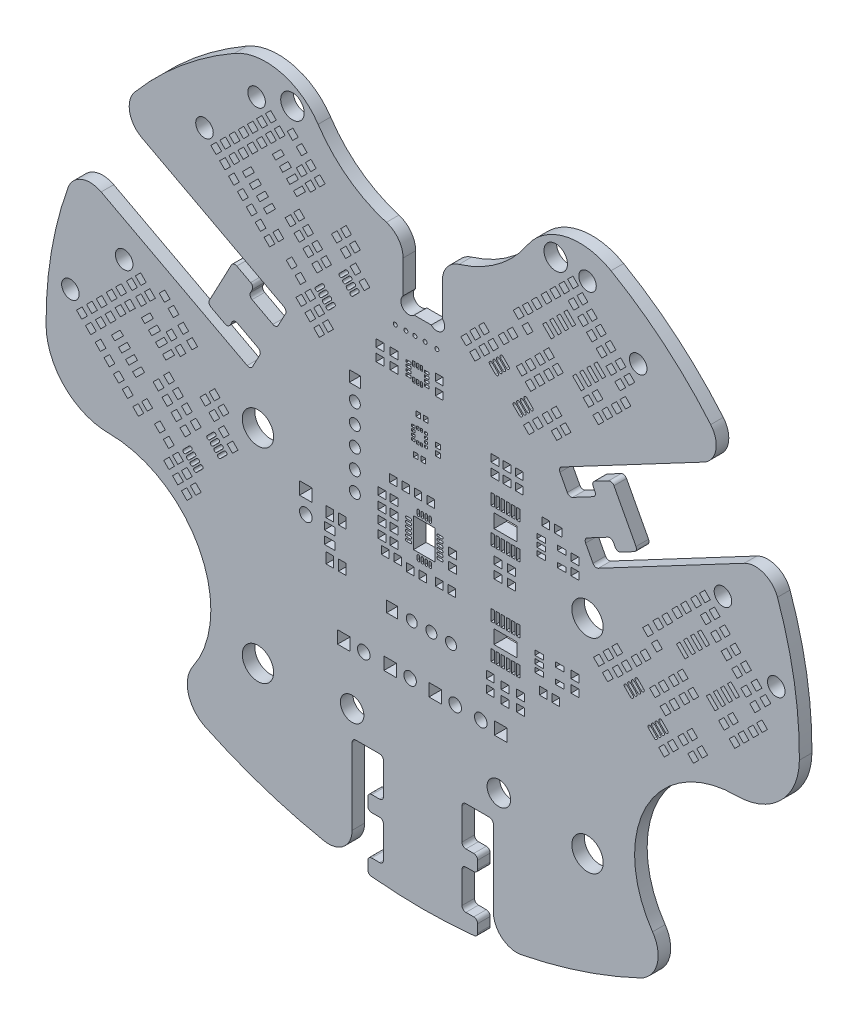
SolidWorks part; units mm, degrees
ref_plane "Plan de face" through (0, 0, 0) normal (0, 0, 1) x (1, 0, 0)
ref_plane "Plan de dessus" through (0, 0, 0) normal (0, 1, 0) x (1, 0, 0)
ref_plane "Plan de droite" through (0, 0, 0) normal (1, 0, 0) x (0, 0, -1)
sketch "Model" plane through (0, 0, 0) normal (0, 0, 1) x (1, 0, 0)
  line L0 (-9.8, 40.25) -> (-8.4, 40.25)
  line L1 (-8.4, 40.25) -> (-8.4, 38.85)
  line L2 (-8.4, 38.85) -> (-9.8, 38.85)
  line L3 (-9.8, 38.85) -> (-9.8, 40.25)
  line L4 (0.15, 36.75) -> (0.15, 36.45)
  line L5 (0.15, 36.45) -> (-0.25, 36.45)
  line L6 (-0.25, 36.45) -> (-0.25, 36.75)
  line L7 (-0.25, 36.75) -> (0.15, 36.75)
  line L8 (0.15, 37.25) -> (0.15, 36.95)
  line L9 (0.15, 36.95) -> (-0.25, 36.95)
  line L10 (-0.25, 36.95) -> (-0.25, 37.25)
  line L11 (-0.25, 37.25) -> (0.15, 37.25)
  line L12 (0.15, 37.75) -> (0.15, 37.45)
  line L13 (0.15, 37.45) -> (-0.25, 37.45)
  line L14 (-0.25, 37.45) -> (-0.25, 37.75)
  line L15 (-0.25, 37.75) -> (0.15, 37.75)
  line L16 (0.15, 38.25) -> (0.15, 37.95)
  line L17 (0.15, 37.95) -> (-0.25, 37.95)
  line L18 (-0.25, 37.95) -> (-0.25, 38.25)
  line L19 (-0.25, 38.25) -> (0.15, 38.25)
  line L20 (-0.75, 38.35) -> (-0.45, 38.35)
  line L21 (-0.45, 38.35) -> (-0.45, 37.95)
  line L22 (-0.45, 37.95) -> (-0.75, 37.95)
  line L23 (-0.75, 37.95) -> (-0.75, 38.35)
  line L24 (-1.25, 38.35) -> (-0.95, 38.35)
  line L25 (-0.95, 38.35) -> (-0.95, 37.95)
  line L26 (-0.95, 37.95) -> (-1.25, 37.95)
  line L27 (-1.25, 37.95) -> (-1.25, 38.35)
  line L28 (-1.45, 38.25) -> (-1.45, 37.95)
  line L29 (-1.45, 37.95) -> (-1.85, 37.95)
  line L30 (-1.85, 37.95) -> (-1.85, 38.25)
  line L31 (-1.85, 38.25) -> (-1.45, 38.25)
  line L32 (-1.45, 37.75) -> (-1.45, 37.45)
  line L33 (-1.45, 37.45) -> (-1.85, 37.45)
  line L34 (-1.85, 37.45) -> (-1.85, 37.75)
  line L35 (-1.85, 37.75) -> (-1.45, 37.75)
  line L36 (-1.45, 37.25) -> (-1.45, 36.95)
  line L37 (-1.45, 36.95) -> (-1.85, 36.95)
  line L38 (-1.85, 36.95) -> (-1.85, 37.25)
  line L39 (-1.85, 37.25) -> (-1.45, 37.25)
  line L40 (-1.45, 36.75) -> (-1.45, 36.45)
  line L41 (-1.45, 36.45) -> (-1.85, 36.45)
  line L42 (-1.85, 36.45) -> (-1.85, 36.75)
  line L43 (-1.85, 36.75) -> (-1.45, 36.75)
  line L44 (-1.25, 36.75) -> (-0.95, 36.75)
  line L45 (-0.95, 36.75) -> (-0.95, 36.35)
  line L46 (-0.95, 36.35) -> (-1.25, 36.35)
  line L47 (-1.25, 36.35) -> (-1.25, 36.75)
  line L48 (-0.75, 36.75) -> (-0.45, 36.75)
  line L49 (-0.45, 36.75) -> (-0.45, 36.35)
  line L50 (-0.45, 36.35) -> (-0.75, 36.35)
  line L51 (-0.75, 36.35) -> (-0.75, 36.75)
  line L52 (13.85, 20.55) -> (13.85, 21.15)
  line L53 (13.85, 21.15) -> (14.95, 21.15)
  line L54 (14.95, 21.15) -> (14.95, 20.55)
  line L55 (14.95, 20.55) -> (13.85, 20.55)
  line L56 (13.85, 19.6) -> (13.85, 20.2)
  line L57 (13.85, 20.2) -> (14.95, 20.2)
  line L58 (14.95, 20.2) -> (14.95, 19.6)
  line L59 (14.95, 19.6) -> (13.85, 19.6)
  line L60 (13.85, 18.65) -> (13.85, 19.25)
  line L61 (13.85, 19.25) -> (14.95, 19.25)
  line L62 (14.95, 19.25) -> (14.95, 18.65)
  line L63 (14.95, 18.65) -> (13.85, 18.65)
  line L64 (16.45, 18.65) -> (16.45, 19.25)
  line L65 (16.45, 19.25) -> (17.55, 19.25)
  line L66 (17.55, 19.25) -> (17.55, 18.65)
  line L67 (17.55, 18.65) -> (16.45, 18.65)
  line L68 (16.45, 20.55) -> (16.45, 21.15)
  line L69 (16.45, 21.15) -> (17.55, 21.15)
  line L70 (17.55, 21.15) -> (17.55, 20.55)
  line L71 (17.55, 20.55) -> (16.45, 20.55)
  line L72 (14.1, 33.55) -> (14.1, 34.15)
  line L73 (14.1, 34.15) -> (15.2, 34.15)
  line L74 (15.2, 34.15) -> (15.2, 33.55)
  line L75 (15.2, 33.55) -> (14.1, 33.55)
  line L76 (14.1, 32.6) -> (14.1, 33.2)
  line L77 (14.1, 33.2) -> (15.2, 33.2)
  line L78 (15.2, 33.2) -> (15.2, 32.6)
  line L79 (15.2, 32.6) -> (14.1, 32.6)
  line L80 (14.1, 31.65) -> (14.1, 32.25)
  line L81 (14.1, 32.25) -> (15.2, 32.25)
  line L82 (15.2, 32.25) -> (15.2, 31.65)
  line L83 (15.2, 31.65) -> (14.1, 31.65)
  line L84 (16.7, 31.65) -> (16.7, 32.25)
  line L85 (16.7, 32.25) -> (17.8, 32.25)
  line L86 (17.8, 32.25) -> (17.8, 31.65)
  line L87 (17.8, 31.65) -> (16.7, 31.65)
  line L88 (16.7, 33.55) -> (16.7, 34.15)
  line L89 (16.7, 34.15) -> (17.8, 34.15)
  line L90 (17.8, 34.15) -> (17.8, 33.55)
  line L91 (17.8, 33.55) -> (16.7, 33.55)
  line L92 (1.82, 36.815) -> (1.82, 36.225)
  line L93 (1.82, 36.225) -> (1.18, 36.225)
  line L94 (1.18, 36.225) -> (1.18, 36.815)
  line L95 (1.18, 36.815) -> (1.82, 36.815)
  line L96 (1.82, 37.775) -> (1.82, 37.185)
  line L97 (1.82, 37.185) -> (1.18, 37.185)
  line L98 (1.18, 37.185) -> (1.18, 37.775)
  line L99 (1.18, 37.775) -> (1.82, 37.775)
  line L100 (-0.665, 35.32) -> (-0.075, 35.32)
  line L101 (-0.075, 35.32) -> (-0.075, 34.68)
  line L102 (-0.075, 34.68) -> (-0.665, 34.68)
  line L103 (-0.665, 34.68) -> (-0.665, 35.32)
  line L104 (-1.625, 35.32) -> (-1.035, 35.32)
  line L105 (-1.035, 35.32) -> (-1.035, 34.68)
  line L106 (-1.035, 34.68) -> (-1.625, 34.68)
  line L107 (-1.625, 34.68) -> (-1.625, 35.32)
  line L108 (-0.365, 39.97) -> (0.225, 39.97)
  line L109 (0.225, 39.97) -> (0.225, 39.33)
  line L110 (0.225, 39.33) -> (-0.365, 39.33)
  line L111 (-0.365, 39.33) -> (-0.365, 39.97)
  line L112 (-1.325, 39.97) -> (-0.735, 39.97)
  line L113 (-0.735, 39.97) -> (-0.735, 39.33)
  line L114 (-0.735, 39.33) -> (-1.325, 39.33)
  line L115 (-1.325, 39.33) -> (-1.325, 39.97)
  line L116 (-11.175, 23.775) -> (-10.225, 23.775)
  line L117 (-10.225, 23.775) -> (-10.225, 22.425)
  line L118 (-10.225, 22.425) -> (-11.175, 22.425)
  line L119 (-11.175, 22.425) -> (-11.175, 23.775)
  line L120 (-12.775, 23.775) -> (-11.825, 23.775)
  line L121 (-11.825, 23.775) -> (-11.825, 22.425)
  line L122 (-11.825, 22.425) -> (-12.775, 22.425)
  line L123 (-12.775, 22.425) -> (-12.775, 23.775)
  line L124 (-11.175, 18.675) -> (-10.225, 18.675)
  line L125 (-10.225, 18.675) -> (-10.225, 17.325)
  line L126 (-10.225, 17.325) -> (-11.175, 17.325)
  line L127 (-11.175, 17.325) -> (-11.175, 18.675)
  line L128 (-12.775, 18.675) -> (-11.825, 18.675)
  line L129 (-11.825, 18.675) -> (-11.825, 17.325)
  line L130 (-11.825, 17.325) -> (-12.775, 17.325)
  line L131 (-12.775, 17.325) -> (-12.775, 18.675)
  line L132 (-12.975, 20.975) -> (-12.975, 21.925)
  line L133 (-12.975, 21.925) -> (-11.625, 21.925)
  line L134 (-11.625, 21.925) -> (-11.625, 20.975)
  line L135 (-11.625, 20.975) -> (-12.975, 20.975)
  line L136 (-12.975, 19.375) -> (-12.975, 20.325)
  line L137 (-12.975, 20.325) -> (-11.625, 20.325)
  line L138 (-11.625, 20.325) -> (-11.625, 19.375)
  line L139 (-11.625, 19.375) -> (-12.975, 19.375)
  line L140 (27.3989, 23.429) -> (26.6565, 24.1714)
  line L141 (26.9747, 24.4896) -> (27.7171, 23.7472)
  line L142 (26.9393, 22.9694) -> (26.1969, 23.7118)
  line L143 (26.5151, 24.03) -> (27.2575, 23.2876)
  line L144 (26.4797, 22.5098) -> (25.7373, 23.2522)
  line L145 (26.0555, 23.5704) -> (26.7979, 22.828)
  line L146 (26.0201, 22.0502) -> (25.2777, 22.7926)
  line L147 (25.5959, 23.1108) -> (26.3383, 22.3684)
  line L148 (29.0607, 19.0096) -> (28.3183, 19.752)
  line L149 (28.6365, 20.0702) -> (29.3789, 19.3278)
  line L150 (29.5203, 19.4692) -> (28.7779, 20.2116)
  line L151 (29.0961, 20.5298) -> (29.8385, 19.7874)
  line L152 (29.9799, 19.9288) -> (29.2375, 20.6712)
  line L153 (29.5557, 20.9894) -> (30.2981, 20.247)
  line L154 (30.4395, 20.3884) -> (29.6971, 21.1308)
  line L155 (30.0153, 21.449) -> (30.7577, 20.7066)
  line L156 (-29.8922, 21.3049) -> (-30.6346, 20.5625)
  line L157 (-30.9528, 20.8807) -> (-30.2104, 21.6231)
  line L158 (-29.4326, 20.8453) -> (-30.175, 20.1029)
  line L159 (-30.4932, 20.4211) -> (-29.7508, 21.1635)
  line L160 (-28.973, 20.3857) -> (-29.7154, 19.6433)
  line L161 (-30.0336, 19.9615) -> (-29.2912, 20.7039)
  line L162 (-28.5134, 19.9261) -> (-29.2558, 19.1837)
  line L163 (-29.574, 19.5019) -> (-28.8316, 20.2443)
  line L164 (-25.4728, 22.9667) -> (-26.2152, 22.2243)
  line L165 (-26.5334, 22.5425) -> (-25.791, 23.2849)
  line L166 (-25.9324, 23.4263) -> (-26.6748, 22.6839)
  line L167 (-26.993, 23.0021) -> (-26.2506, 23.7445)
  line L168 (-26.392, 23.8859) -> (-27.1344, 23.1435)
  line L169 (-27.4526, 23.4617) -> (-26.7102, 24.2041)
  line L170 (-26.8516, 24.3455) -> (-27.594, 23.6031)
  line L171 (-27.9122, 23.9213) -> (-27.1698, 24.6637)
  line L172 (10.2055, 50.428) -> (9.4631, 51.1704)
  line L173 (9.7813, 51.4886) -> (10.5237, 50.7462)
  line L174 (9.7459, 49.9684) -> (9.0035, 50.7108)
  line L175 (9.3217, 51.029) -> (10.0641, 50.2866)
  line L176 (9.2863, 49.5088) -> (8.5439, 50.2512)
  line L177 (8.8621, 50.5694) -> (9.6045, 49.827)
  line L178 (8.8267, 49.0492) -> (8.0843, 49.7916)
  line L179 (8.4025, 50.1098) -> (9.1449, 49.3674)
  line L180 (11.8673, 46.0086) -> (11.1249, 46.751)
  line L181 (11.4431, 47.0692) -> (12.1855, 46.3268)
  line L182 (12.3269, 46.4682) -> (11.5845, 47.2106)
  line L183 (11.9027, 47.5288) -> (12.6451, 46.7864)
  line L184 (12.7865, 46.9278) -> (12.0441, 47.6702)
  line L185 (12.3623, 47.9884) -> (13.1047, 47.246)
  line L186 (13.2461, 47.3874) -> (12.5037, 48.1298)
  line L187 (12.8219, 48.448) -> (13.5643, 47.7056)
  line L188 (-13.0317, 47.6509) -> (-13.7741, 46.9085)
  line L189 (-14.0923, 47.2267) -> (-13.3499, 47.9691)
  line L190 (-12.5721, 47.1913) -> (-13.3145, 46.4489)
  line L191 (-13.6327, 46.7671) -> (-12.8903, 47.5095)
  line L192 (-12.1125, 46.7317) -> (-12.8549, 45.9893)
  line L193 (-13.1731, 46.3075) -> (-12.4307, 47.0499)
  line L194 (-11.6529, 46.2721) -> (-12.3953, 45.5297)
  line L195 (-12.7135, 45.8479) -> (-11.9711, 46.5903)
  line L196 (-8.6123, 49.3127) -> (-9.3547, 48.5703)
  line L197 (-9.6729, 48.8885) -> (-8.9305, 49.6309)
  line L198 (-9.0719, 49.7723) -> (-9.8143, 49.0299)
  line L199 (-10.1325, 49.3481) -> (-9.3901, 50.0905)
  line L200 (-9.5315, 50.2319) -> (-10.2739, 49.4895)
  line L201 (-10.5921, 49.8077) -> (-9.8497, 50.5501)
  line L202 (-9.9911, 50.6915) -> (-10.7335, 49.9491)
  line L203 (-11.0517, 50.2673) -> (-10.3093, 51.0097)
  line L204 (37.2241, 26.3246) -> (36.7999, 25.9004)
  line L205 (36.7999, 25.9004) -> (35.7039, 26.9964)
  line L206 (35.7039, 26.9964) -> (36.1281, 27.4206)
  line L207 (36.1281, 27.4206) -> (37.2241, 26.3246)
  line L208 (38.1222, 27.2226) -> (37.698, 26.7984)
  line L209 (37.698, 26.7984) -> (36.602, 27.8944)
  line L210 (36.602, 27.8944) -> (37.0262, 28.3186)
  line L211 (37.0262, 28.3186) -> (38.1222, 27.2226)
  line L212 (39.0202, 28.1206) -> (38.596, 27.6964)
  line L213 (38.596, 27.6964) -> (37.5, 28.7924)
  line L214 (37.5, 28.7924) -> (37.9242, 29.2166)
  line L215 (37.9242, 29.2166) -> (39.0202, 28.1206)
  line L216 (39.9182, 29.0187) -> (39.494, 28.5945)
  line L217 (39.494, 28.5945) -> (38.398, 29.6905)
  line L218 (38.398, 29.6905) -> (38.8222, 30.1147)
  line L219 (38.8222, 30.1147) -> (39.9182, 29.0187)
  line L220 (36.0999, 32.837) -> (35.6757, 32.4128)
  line L221 (35.6757, 32.4128) -> (34.5797, 33.5088)
  line L222 (34.5797, 33.5088) -> (35.0039, 33.933)
  line L223 (35.0039, 33.933) -> (36.0999, 32.837)
  line L224 (35.2018, 31.939) -> (34.7776, 31.5148)
  line L225 (34.7776, 31.5148) -> (33.6816, 32.6108)
  line L226 (33.6816, 32.6108) -> (34.1058, 33.035)
  line L227 (34.1058, 33.035) -> (35.2018, 31.939)
  line L228 (34.3038, 31.041) -> (33.8796, 30.6168)
  line L229 (33.8796, 30.6168) -> (32.7836, 31.7128)
  line L230 (32.7836, 31.7128) -> (33.2078, 32.137)
  line L231 (33.2078, 32.137) -> (34.3038, 31.041)
  line L232 (33.4058, 30.1429) -> (32.9816, 29.7187)
  line L233 (32.9816, 29.7187) -> (31.8856, 30.8147)
  line L234 (31.8856, 30.8147) -> (32.3098, 31.2389)
  line L235 (32.3098, 31.2389) -> (33.4058, 30.1429)
  line L236 (-32.505, 31.1302) -> (-32.0808, 30.706)
  line L237 (-32.0808, 30.706) -> (-33.1768, 29.61)
  line L238 (-33.1768, 29.61) -> (-33.601, 30.0342)
  line L239 (-33.601, 30.0342) -> (-32.505, 31.1302)
  line L240 (-33.403, 32.0283) -> (-32.9788, 31.6041)
  line L241 (-32.9788, 31.6041) -> (-34.0748, 30.5081)
  line L242 (-34.0748, 30.5081) -> (-34.499, 30.9323)
  line L243 (-34.499, 30.9323) -> (-33.403, 32.0283)
  line L244 (-34.301, 32.9263) -> (-33.8768, 32.5021)
  line L245 (-33.8768, 32.5021) -> (-34.9728, 31.4061)
  line L246 (-34.9728, 31.4061) -> (-35.397, 31.8303)
  line L247 (-35.397, 31.8303) -> (-34.301, 32.9263)
  line L248 (-35.1991, 33.8243) -> (-34.7749, 33.4001)
  line L249 (-34.7749, 33.4001) -> (-35.8709, 32.3041)
  line L250 (-35.8709, 32.3041) -> (-36.2951, 32.7283)
  line L251 (-36.2951, 32.7283) -> (-35.1991, 33.8243)
  line L252 (-39.0174, 30.006) -> (-38.5932, 29.5818)
  line L253 (-38.5932, 29.5818) -> (-39.6892, 28.4858)
  line L254 (-39.6892, 28.4858) -> (-40.1134, 28.91)
  line L255 (-40.1134, 28.91) -> (-39.0174, 30.006)
  line L256 (-38.1194, 29.1079) -> (-37.6952, 28.6837)
  line L257 (-37.6952, 28.6837) -> (-38.7912, 27.5877)
  line L258 (-38.7912, 27.5877) -> (-39.2154, 28.0119)
  line L259 (-39.2154, 28.0119) -> (-38.1194, 29.1079)
  line L260 (-37.2214, 28.2099) -> (-36.7972, 27.7857)
  line L261 (-36.7972, 27.7857) -> (-37.8932, 26.6897)
  line L262 (-37.8932, 26.6897) -> (-38.3174, 27.1139)
  line L263 (-38.3174, 27.1139) -> (-37.2214, 28.2099)
  line L264 (-36.3233, 27.3119) -> (-35.8991, 26.8877)
  line L265 (-35.8991, 26.8877) -> (-36.9951, 25.7917)
  line L266 (-36.9951, 25.7917) -> (-37.4193, 26.2159)
  line L267 (-37.4193, 26.2159) -> (-36.3233, 27.3119)
  line L268 (20.1722, 53.1115) -> (19.748, 52.6873)
  line L269 (19.748, 52.6873) -> (18.652, 53.7833)
  line L270 (18.652, 53.7833) -> (19.0762, 54.2075)
  line L271 (19.0762, 54.2075) -> (20.1722, 53.1115)
  line L272 (21.0703, 54.0095) -> (20.6461, 53.5853)
  line L273 (20.6461, 53.5853) -> (19.5501, 54.6813)
  line L274 (19.5501, 54.6813) -> (19.9743, 55.1055)
  line L275 (19.9743, 55.1055) -> (21.0703, 54.0095)
  line L276 (21.9683, 54.9075) -> (21.5441, 54.4833)
  line L277 (21.5441, 54.4833) -> (20.4481, 55.5793)
  line L278 (20.4481, 55.5793) -> (20.8723, 56.0035)
  line L279 (20.8723, 56.0035) -> (21.9683, 54.9075)
  line L280 (22.8663, 55.8056) -> (22.4421, 55.3814)
  line L281 (22.4421, 55.3814) -> (21.3461, 56.4774)
  line L282 (21.3461, 56.4774) -> (21.7703, 56.9016)
  line L283 (21.7703, 56.9016) -> (22.8663, 55.8056)
  line L284 (19.048, 59.6239) -> (18.6238, 59.1997)
  line L285 (18.6238, 59.1997) -> (17.5278, 60.2957)
  line L286 (17.5278, 60.2957) -> (17.952, 60.7199)
  line L287 (17.952, 60.7199) -> (19.048, 59.6239)
  line L288 (18.1499, 58.7259) -> (17.7257, 58.3017)
  line L289 (17.7257, 58.3017) -> (16.6297, 59.3977)
  line L290 (16.6297, 59.3977) -> (17.0539, 59.8219)
  line L291 (17.0539, 59.8219) -> (18.1499, 58.7259)
  line L292 (17.2519, 57.8279) -> (16.8277, 57.4037)
  line L293 (16.8277, 57.4037) -> (15.7317, 58.4997)
  line L294 (15.7317, 58.4997) -> (16.1559, 58.9239)
  line L295 (16.1559, 58.9239) -> (17.2519, 57.8279)
  line L296 (16.3539, 56.9298) -> (15.9297, 56.5056)
  line L297 (15.9297, 56.5056) -> (14.8337, 57.6016)
  line L298 (14.8337, 57.6016) -> (15.2579, 58.0258)
  line L299 (15.2579, 58.0258) -> (16.3539, 56.9298)
  line L300 (-15.8213, 57.5115) -> (-15.3971, 57.0873)
  line L301 (-15.3971, 57.0873) -> (-16.4931, 55.9913)
  line L302 (-16.4931, 55.9913) -> (-16.9173, 56.4155)
  line L303 (-16.9173, 56.4155) -> (-15.8213, 57.5115)
  line L304 (-16.7193, 58.4096) -> (-16.2951, 57.9854)
  line L305 (-16.2951, 57.9854) -> (-17.3911, 56.8894)
  line L306 (-17.3911, 56.8894) -> (-17.8153, 57.3136)
  line L307 (-17.8153, 57.3136) -> (-16.7193, 58.4096)
  line L308 (-17.6173, 59.3076) -> (-17.1931, 58.8834)
  line L309 (-17.1931, 58.8834) -> (-18.2891, 57.7874)
  line L310 (-18.2891, 57.7874) -> (-18.7133, 58.2116)
  line L311 (-18.7133, 58.2116) -> (-17.6173, 59.3076)
  line L312 (-18.5154, 60.2056) -> (-18.0912, 59.7814)
  line L313 (-18.0912, 59.7814) -> (-19.1872, 58.6854)
  line L314 (-19.1872, 58.6854) -> (-19.6114, 59.1096)
  line L315 (-19.6114, 59.1096) -> (-18.5154, 60.2056)
  line L316 (-22.3337, 56.3873) -> (-21.9095, 55.9631)
  line L317 (-21.9095, 55.9631) -> (-23.0055, 54.8671)
  line L318 (-23.0055, 54.8671) -> (-23.4297, 55.2913)
  line L319 (-23.4297, 55.2913) -> (-22.3337, 56.3873)
  line L320 (-21.4357, 55.4892) -> (-21.0115, 55.065)
  line L321 (-21.0115, 55.065) -> (-22.1075, 53.969)
  line L322 (-22.1075, 53.969) -> (-22.5317, 54.3932)
  line L323 (-22.5317, 54.3932) -> (-21.4357, 55.4892)
  line L324 (-20.5377, 54.5912) -> (-20.1135, 54.167)
  line L325 (-20.1135, 54.167) -> (-21.2095, 53.071)
  line L326 (-21.2095, 53.071) -> (-21.6337, 53.4952)
  line L327 (-21.6337, 53.4952) -> (-20.5377, 54.5912)
  line L328 (-19.6396, 53.6932) -> (-19.2154, 53.269)
  line L329 (-19.2154, 53.269) -> (-20.3114, 52.173)
  line L330 (-20.3114, 52.173) -> (-20.7356, 52.5972)
  line L331 (-20.7356, 52.5972) -> (-19.6396, 53.6932)
  line L332 (1.5, 25.25) -> (2, 25.25)
  line L333 (2, 24.95) -> (1.5, 24.95)
  line L334 (1.5, 25.75) -> (2, 25.75)
  line L335 (2, 25.45) -> (1.5, 25.45)
  line L336 (1.5, 26.25) -> (2, 26.25)
  line L337 (2, 25.95) -> (1.5, 25.95)
  line L338 (1.5, 26.75) -> (2, 26.75)
  line L339 (2, 26.45) -> (1.5, 26.45)
  line L340 (1.5, 27.25) -> (2, 27.25)
  line L341 (2, 26.95) -> (1.5, 26.95)
  line L342 (1.5, 27.75) -> (2, 27.75)
  line L343 (2, 27.45) -> (1.5, 27.45)
  line L344 (0.35, 28.6) -> (0.35, 29.1)
  line L345 (0.65, 29.1) -> (0.65, 28.6)
  line L346 (-0.15, 28.6) -> (-0.15, 29.1)
  line L347 (0.15, 29.1) -> (0.15, 28.6)
  line L348 (-0.65, 28.6) -> (-0.65, 29.1)
  line L349 (-0.35, 29.1) -> (-0.35, 28.6)
  line L350 (-1.15, 28.6) -> (-1.15, 29.1)
  line L351 (-0.85, 29.1) -> (-0.85, 28.6)
  line L352 (-2.5, 27.75) -> (-2, 27.75)
  line L353 (-2, 27.45) -> (-2.5, 27.45)
  line L354 (-2.5, 27.25) -> (-2, 27.25)
  line L355 (-2, 26.95) -> (-2.5, 26.95)
  line L356 (-2.5, 26.75) -> (-2, 26.75)
  line L357 (-2, 26.45) -> (-2.5, 26.45)
  line L358 (-2.5, 26.25) -> (-2, 26.25)
  line L359 (-2, 25.95) -> (-2.5, 25.95)
  line L360 (-2.5, 25.75) -> (-2, 25.75)
  line L361 (-2, 25.45) -> (-2.5, 25.45)
  line L362 (-2.5, 25.25) -> (-2, 25.25)
  line L363 (-2, 24.95) -> (-2.5, 24.95)
  line L364 (-1.15, 23.6) -> (-1.15, 24.1)
  line L365 (-0.85, 24.1) -> (-0.85, 23.6)
  line L366 (-0.65, 23.6) -> (-0.65, 24.1)
  line L367 (-0.35, 24.1) -> (-0.35, 23.6)
  line L368 (-0.15, 23.6) -> (-0.15, 24.1)
  line L369 (0.15, 24.1) -> (0.15, 23.6)
  line L370 (0.35, 23.6) -> (0.35, 24.1)
  line L371 (0.65, 24.1) -> (0.65, 23.6)
  line L372 (1.125, 28.225) -> (1.125, 24.475)
  line L373 (1.125, 24.475) -> (-1.625, 24.475)
  line L374 (-1.625, 24.475) -> (-1.625, 28.225)
  line L375 (-1.625, 28.225) -> (1.125, 28.225)
  line L376 (8.7, 31.3005) -> (8.7, 29.8755)
  line L377 (8.7, 29.8755) -> (8.25, 29.8755)
  line L378 (8.25, 29.8755) -> (8.25, 31.3005)
  line L379 (8.25, 31.3005) -> (8.7, 31.3005)
  line L380 (9.35, 31.3005) -> (9.35, 29.8755)
  line L381 (9.35, 29.8755) -> (8.9, 29.8755)
  line L382 (8.9, 29.8755) -> (8.9, 31.3005)
  line L383 (8.9, 31.3005) -> (9.35, 31.3005)
  line L384 (10, 31.3005) -> (10, 29.8755)
  line L385 (10, 29.8755) -> (9.55, 29.8755)
  line L386 (9.55, 29.8755) -> (9.55, 31.3005)
  line L387 (9.55, 31.3005) -> (10, 31.3005)
  line L388 (10.65, 31.3005) -> (10.65, 29.8755)
  line L389 (10.65, 29.8755) -> (10.2, 29.8755)
  line L390 (10.2, 29.8755) -> (10.2, 31.3005)
  line L391 (10.2, 31.3005) -> (10.65, 31.3005)
  line L392 (11.3, 31.3005) -> (11.3, 29.8755)
  line L393 (11.3, 29.8755) -> (10.85, 29.8755)
  line L394 (10.85, 29.8755) -> (10.85, 31.3005)
  line L395 (10.85, 31.3005) -> (11.3, 31.3005)
  line L396 (11.95, 31.3005) -> (11.95, 29.8755)
  line L397 (11.95, 29.8755) -> (11.5, 29.8755)
  line L398 (11.5, 29.8755) -> (11.5, 31.3005)
  line L399 (11.5, 31.3005) -> (11.95, 31.3005)
  line L400 (11.95, 35.7245) -> (11.95, 34.2995)
  line L401 (11.95, 34.2995) -> (11.5, 34.2995)
  line L402 (11.5, 34.2995) -> (11.5, 35.7245)
  line L403 (11.5, 35.7245) -> (11.95, 35.7245)
  line L404 (11.3, 35.7245) -> (11.3, 34.2995)
  line L405 (11.3, 34.2995) -> (10.85, 34.2995)
  line L406 (10.85, 34.2995) -> (10.85, 35.7245)
  line L407 (10.85, 35.7245) -> (11.3, 35.7245)
  line L408 (10.65, 35.7245) -> (10.65, 34.2995)
  line L409 (10.65, 34.2995) -> (10.2, 34.2995)
  line L410 (10.2, 34.2995) -> (10.2, 35.7245)
  line L411 (10.2, 35.7245) -> (10.65, 35.7245)
  line L412 (10, 35.7245) -> (10, 34.2995)
  line L413 (10, 34.2995) -> (9.55, 34.2995)
  line L414 (9.55, 34.2995) -> (9.55, 35.7245)
  line L415 (9.55, 35.7245) -> (10, 35.7245)
  line L416 (9.35, 35.7245) -> (9.35, 34.2995)
  line L417 (9.35, 34.2995) -> (8.9, 34.2995)
  line L418 (8.9, 34.2995) -> (8.9, 35.7245)
  line L419 (8.9, 35.7245) -> (9.35, 35.7245)
  line L420 (8.7, 35.7245) -> (8.7, 34.2995)
  line L421 (8.7, 34.2995) -> (8.25, 34.2995)
  line L422 (8.25, 34.2995) -> (8.25, 35.7245)
  line L423 (8.25, 35.7245) -> (8.7, 35.7245)
  line L424 (8.6265, 33.6765) -> (11.5735, 33.6765)
  line L425 (11.5735, 33.6765) -> (11.5735, 31.9235)
  line L426 (11.5735, 31.9235) -> (8.6265, 31.9235)
  line L427 (8.6265, 31.9235) -> (8.6265, 33.6765)
  line L428 (11.5, 21.4995) -> (11.5, 22.9245)
  line L429 (11.5, 22.9245) -> (11.95, 22.9245)
  line L430 (11.95, 22.9245) -> (11.95, 21.4995)
  line L431 (11.95, 21.4995) -> (11.5, 21.4995)
  line L432 (10.85, 21.4995) -> (10.85, 22.9245)
  line L433 (10.85, 22.9245) -> (11.3, 22.9245)
  line L434 (11.3, 22.9245) -> (11.3, 21.4995)
  line L435 (11.3, 21.4995) -> (10.85, 21.4995)
  line L436 (10.2, 21.4995) -> (10.2, 22.9245)
  line L437 (10.2, 22.9245) -> (10.65, 22.9245)
  line L438 (10.65, 22.9245) -> (10.65, 21.4995)
  line L439 (10.65, 21.4995) -> (10.2, 21.4995)
  line L440 (9.55, 21.4995) -> (9.55, 22.9245)
  line L441 (9.55, 22.9245) -> (10, 22.9245)
  line L442 (10, 22.9245) -> (10, 21.4995)
  line L443 (10, 21.4995) -> (9.55, 21.4995)
  line L444 (8.9, 21.4995) -> (8.9, 22.9245)
  line L445 (8.9, 22.9245) -> (9.35, 22.9245)
  line L446 (9.35, 22.9245) -> (9.35, 21.4995)
  line L447 (9.35, 21.4995) -> (8.9, 21.4995)
  line L448 (8.25, 21.4995) -> (8.25, 22.9245)
  line L449 (8.25, 22.9245) -> (8.7, 22.9245)
  line L450 (8.7, 22.9245) -> (8.7, 21.4995)
  line L451 (8.7, 21.4995) -> (8.25, 21.4995)
  line L452 (8.25, 17.0755) -> (8.25, 18.5005)
  line L453 (8.25, 18.5005) -> (8.7, 18.5005)
  line L454 (8.7, 18.5005) -> (8.7, 17.0755)
  line L455 (8.7, 17.0755) -> (8.25, 17.0755)
  line L456 (8.9, 17.0755) -> (8.9, 18.5005)
  line L457 (8.9, 18.5005) -> (9.35, 18.5005)
  line L458 (9.35, 18.5005) -> (9.35, 17.0755)
  line L459 (9.35, 17.0755) -> (8.9, 17.0755)
  line L460 (9.55, 17.0755) -> (9.55, 18.5005)
  line L461 (9.55, 18.5005) -> (10, 18.5005)
  line L462 (10, 18.5005) -> (10, 17.0755)
  line L463 (10, 17.0755) -> (9.55, 17.0755)
  line L464 (10.2, 17.0755) -> (10.2, 18.5005)
  line L465 (10.2, 18.5005) -> (10.65, 18.5005)
  line L466 (10.65, 18.5005) -> (10.65, 17.0755)
  line L467 (10.65, 17.0755) -> (10.2, 17.0755)
  line L468 (10.85, 17.0755) -> (10.85, 18.5005)
  line L469 (10.85, 18.5005) -> (11.3, 18.5005)
  line L470 (11.3, 18.5005) -> (11.3, 17.0755)
  line L471 (11.3, 17.0755) -> (10.85, 17.0755)
  line L472 (11.5, 17.0755) -> (11.5, 18.5005)
  line L473 (11.5, 18.5005) -> (11.95, 18.5005)
  line L474 (11.95, 18.5005) -> (11.95, 17.0755)
  line L475 (11.95, 17.0755) -> (11.5, 17.0755)
  line L476 (11.5735, 19.1235) -> (8.6265, 19.1235)
  line L477 (8.6265, 19.1235) -> (8.6265, 20.8765)
  line L478 (8.6265, 20.8765) -> (11.5735, 20.8765)
  line L479 (11.5735, 20.8765) -> (11.5735, 19.1235)
  line L480 (0.35, 43.5) -> (0.35, 43.2)
  line L481 (0.35, 43.2) -> (-0.25, 43.2)
  line L482 (-0.25, 43.2) -> (-0.25, 43.5)
  line L483 (-0.25, 43.5) -> (0.35, 43.5)
  line L484 (0.35, 44) -> (0.35, 43.7)
  line L485 (0.35, 43.7) -> (-0.25, 43.7)
  line L486 (-0.25, 43.7) -> (-0.25, 44)
  line L487 (-0.25, 44) -> (0.35, 44)
  line L488 (0.35, 44.5) -> (0.35, 44.2)
  line L489 (0.35, 44.2) -> (-0.25, 44.2)
  line L490 (-0.25, 44.2) -> (-0.25, 44.5)
  line L491 (-0.25, 44.5) -> (0.35, 44.5)
  line L492 (0.35, 45) -> (0.35, 44.7)
  line L493 (0.35, 44.7) -> (-0.25, 44.7)
  line L494 (-0.25, 44.7) -> (-0.25, 45)
  line L495 (-0.25, 45) -> (0.35, 45)
  line L496 (-0.75, 45.3) -> (-0.45, 45.3)
  line L497 (-0.45, 45.3) -> (-0.45, 44.7)
  line L498 (-0.45, 44.7) -> (-0.75, 44.7)
  line L499 (-0.75, 44.7) -> (-0.75, 45.3)
  line L500 (-1.25, 45.3) -> (-0.95, 45.3)
  line L501 (-0.95, 45.3) -> (-0.95, 44.7)
  line L502 (-0.95, 44.7) -> (-1.25, 44.7)
  line L503 (-1.25, 44.7) -> (-1.25, 45.3)
  line L504 (-1.75, 45.3) -> (-1.45, 45.3)
  line L505 (-1.45, 45.3) -> (-1.45, 44.7)
  line L506 (-1.45, 44.7) -> (-1.75, 44.7)
  line L507 (-1.75, 44.7) -> (-1.75, 45.3)
  line L508 (-1.95, 45) -> (-1.95, 44.7)
  line L509 (-1.95, 44.7) -> (-2.55, 44.7)
  line L510 (-2.55, 44.7) -> (-2.55, 45)
  line L511 (-2.55, 45) -> (-1.95, 45)
  line L512 (-1.95, 44.5) -> (-1.95, 44.2)
  line L513 (-1.95, 44.2) -> (-2.55, 44.2)
  line L514 (-2.55, 44.2) -> (-2.55, 44.5)
  line L515 (-2.55, 44.5) -> (-1.95, 44.5)
  line L516 (-1.95, 44) -> (-1.95, 43.7)
  line L517 (-1.95, 43.7) -> (-2.55, 43.7)
  line L518 (-2.55, 43.7) -> (-2.55, 44)
  line L519 (-2.55, 44) -> (-1.95, 44)
  line L520 (-1.95, 43.5) -> (-1.95, 43.2)
  line L521 (-1.95, 43.2) -> (-2.55, 43.2)
  line L522 (-2.55, 43.2) -> (-2.55, 43.5)
  line L523 (-2.55, 43.5) -> (-1.95, 43.5)
  line L524 (-1.75, 43.5) -> (-1.45, 43.5)
  line L525 (-1.45, 43.5) -> (-1.45, 42.9)
  line L526 (-1.45, 42.9) -> (-1.75, 42.9)
  line L527 (-1.75, 42.9) -> (-1.75, 43.5)
  line L528 (-1.25, 43.5) -> (-0.95, 43.5)
  line L529 (-0.95, 43.5) -> (-0.95, 42.9)
  line L530 (-0.95, 42.9) -> (-1.25, 42.9)
  line L531 (-1.25, 42.9) -> (-1.25, 43.5)
  line L532 (-0.75, 43.5) -> (-0.45, 43.5)
  line L533 (-0.45, 43.5) -> (-0.45, 42.9)
  line L534 (-0.45, 42.9) -> (-0.75, 42.9)
  line L535 (-0.75, 42.9) -> (-0.75, 43.5)
  line L536 (15.375, 16.45) -> (14.425, 16.45)
  line L537 (14.425, 16.45) -> (14.425, 17.45)
  line L538 (14.425, 17.45) -> (15.375, 17.45)
  line L539 (15.375, 17.45) -> (15.375, 16.45)
  line L540 (16.975, 16.45) -> (16.025, 16.45)
  line L541 (16.025, 16.45) -> (16.025, 17.45)
  line L542 (16.025, 17.45) -> (16.975, 17.45)
  line L543 (16.975, 17.45) -> (16.975, 16.45)
  line L544 (15.675, 35.3) -> (14.725, 35.3)
  line L545 (14.725, 35.3) -> (14.725, 36.3)
  line L546 (14.725, 36.3) -> (15.675, 36.3)
  line L547 (15.675, 36.3) -> (15.675, 35.3)
  line L548 (17.275, 35.3) -> (16.325, 35.3)
  line L549 (16.325, 35.3) -> (16.325, 36.3)
  line L550 (16.325, 36.3) -> (17.275, 36.3)
  line L551 (17.275, 36.3) -> (17.275, 35.3)
  line L552 (18.45, 20.275) -> (18.45, 21.225)
  line L553 (18.45, 21.225) -> (19.45, 21.225)
  line L554 (19.45, 21.225) -> (19.45, 20.275)
  line L555 (19.45, 20.275) -> (18.45, 20.275)
  line L556 (18.45, 18.675) -> (18.45, 19.625)
  line L557 (18.45, 19.625) -> (19.45, 19.625)
  line L558 (19.45, 19.625) -> (19.45, 18.675)
  line L559 (19.45, 18.675) -> (18.45, 18.675)
  line L560 (18.45, 33.225) -> (18.45, 34.175)
  line L561 (18.45, 34.175) -> (19.45, 34.175)
  line L562 (19.45, 34.175) -> (19.45, 33.225)
  line L563 (19.45, 33.225) -> (18.45, 33.225)
  line L564 (18.45, 31.625) -> (18.45, 32.575)
  line L565 (18.45, 32.575) -> (19.45, 32.575)
  line L566 (19.45, 32.575) -> (19.45, 31.625)
  line L567 (19.45, 31.625) -> (18.45, 31.625)
  line L568 (27.2576, 27.6363) -> (27.9293, 28.308)
  line L569 (27.9293, 28.308) -> (28.6364, 27.6009)
  line L570 (28.6364, 27.6009) -> (27.9647, 26.9292)
  line L571 (27.9647, 26.9292) -> (27.2576, 27.6363)
  line L572 (26.1262, 26.5049) -> (26.7979, 27.1766)
  line L573 (26.7979, 27.1766) -> (27.505, 26.4695)
  line L574 (27.505, 26.4695) -> (26.8333, 25.7978)
  line L575 (26.8333, 25.7978) -> (26.1262, 26.5049)
  line L576 (32.4194, 35.4852) -> (33.0911, 36.1569)
  line L577 (33.0911, 36.1569) -> (33.7982, 35.4498)
  line L578 (33.7982, 35.4498) -> (33.1265, 34.7781)
  line L579 (33.1265, 34.7781) -> (32.4194, 35.4852)
  line L580 (31.288, 34.3538) -> (31.9597, 35.0255)
  line L581 (31.9597, 35.0255) -> (32.6668, 34.3184)
  line L582 (32.6668, 34.3184) -> (31.9951, 33.6467)
  line L583 (31.9951, 33.6467) -> (31.288, 34.3538)
  line L584 (38.7127, 34.0003) -> (39.3844, 34.672)
  line L585 (39.3844, 34.672) -> (40.0915, 33.9649)
  line L586 (40.0915, 33.9649) -> (39.4198, 33.2932)
  line L587 (39.4198, 33.2932) -> (38.7127, 34.0003)
  line L588 (37.5813, 32.8689) -> (38.253, 33.5406)
  line L589 (38.253, 33.5406) -> (38.9601, 32.8335)
  line L590 (38.9601, 32.8335) -> (38.2884, 32.1618)
  line L591 (38.2884, 32.1618) -> (37.5813, 32.8689)
  line L592 (30.0153, 33.0104) -> (30.687, 33.6821)
  line L593 (30.687, 33.6821) -> (31.3941, 32.975)
  line L594 (31.3941, 32.975) -> (30.7224, 32.3033)
  line L595 (30.7224, 32.3033) -> (30.0153, 33.0104)
  line L596 (28.8839, 31.879) -> (29.5556, 32.5507)
  line L597 (29.5556, 32.5507) -> (30.2627, 31.8436)
  line L598 (30.2627, 31.8436) -> (29.591, 31.1719)
  line L599 (29.591, 31.1719) -> (28.8839, 31.879)
  line L600 (29.591, 25.3736) -> (30.2627, 26.0453)
  line L601 (30.2627, 26.0453) -> (30.9698, 25.3382)
  line L602 (30.9698, 25.3382) -> (30.2981, 24.6665)
  line L603 (30.2981, 24.6665) -> (29.591, 25.3736)
  line L604 (28.4596, 24.2422) -> (29.1313, 24.9139)
  line L605 (29.1313, 24.9139) -> (29.8384, 24.2068)
  line L606 (29.8384, 24.2068) -> (29.1667, 23.5351)
  line L607 (29.1667, 23.5351) -> (28.4596, 24.2422)
  line L608 (37.3692, 35.3438) -> (38.0409, 36.0155)
  line L609 (38.0409, 36.0155) -> (38.748, 35.3084)
  line L610 (38.748, 35.3084) -> (38.0763, 34.6367)
  line L611 (38.0763, 34.6367) -> (37.3692, 35.3438)
  line L612 (36.2378, 34.2124) -> (36.9095, 34.8841)
  line L613 (36.9095, 34.8841) -> (37.6166, 34.177)
  line L614 (37.6166, 34.177) -> (36.9449, 33.5053)
  line L615 (36.9449, 33.5053) -> (36.2378, 34.2124)
  line L616 (30.9345, 24.0301) -> (31.6062, 24.7018)
  line L617 (31.6062, 24.7018) -> (32.3133, 23.9947)
  line L618 (32.3133, 23.9947) -> (31.6416, 23.323)
  line L619 (31.6416, 23.323) -> (30.9345, 24.0301)
  line L620 (29.8031, 22.8987) -> (30.4748, 23.5704)
  line L621 (30.4748, 23.5704) -> (31.1819, 22.8633)
  line L622 (31.1819, 22.8633) -> (30.5102, 22.1916)
  line L623 (30.5102, 22.1916) -> (29.8031, 22.8987)
  line L624 (40.0562, 32.7275) -> (40.7279, 33.3992)
  line L625 (40.7279, 33.3992) -> (41.435, 32.6921)
  line L626 (41.435, 32.6921) -> (40.7633, 32.0204)
  line L627 (40.7633, 32.0204) -> (40.0562, 32.7275)
  line L628 (38.9248, 31.5961) -> (39.5965, 32.2678)
  line L629 (39.5965, 32.2678) -> (40.3036, 31.5607)
  line L630 (40.3036, 31.5607) -> (39.6319, 30.889)
  line L631 (39.6319, 30.889) -> (38.9248, 31.5961)
  line L632 (36.061, 36.652) -> (36.7327, 37.3237)
  line L633 (36.7327, 37.3237) -> (37.4398, 36.6166)
  line L634 (37.4398, 36.6166) -> (36.7681, 35.9449)
  line L635 (36.7681, 35.9449) -> (36.061, 36.652)
  line L636 (34.9296, 35.5206) -> (35.6013, 36.1923)
  line L637 (35.6013, 36.1923) -> (36.3084, 35.4852)
  line L638 (36.3084, 35.4852) -> (35.6367, 34.8135)
  line L639 (35.6367, 34.8135) -> (34.9296, 35.5206)
  line L640 (40.7632, 29.3688) -> (40.0915, 30.0405)
  line L641 (40.0915, 30.0405) -> (40.7986, 30.7476)
  line L642 (40.7986, 30.7476) -> (41.4703, 30.0759)
  line L643 (41.4703, 30.0759) -> (40.7632, 29.3688)
  line L644 (41.8946, 28.2374) -> (41.2229, 28.9091)
  line L645 (41.2229, 28.9091) -> (41.93, 29.6162)
  line L646 (41.93, 29.6162) -> (42.6017, 28.9445)
  line L647 (42.6017, 28.9445) -> (41.8946, 28.2374)
  line L648 (28.2474, 29.793) -> (27.5757, 30.4647)
  line L649 (27.5757, 30.4647) -> (28.2828, 31.1718)
  line L650 (28.2828, 31.1718) -> (28.9545, 30.5001)
  line L651 (28.9545, 30.5001) -> (28.2474, 29.793)
  line L652 (29.3788, 28.6616) -> (28.7071, 29.3333)
  line L653 (28.7071, 29.3333) -> (29.4142, 30.0404)
  line L654 (29.4142, 30.0404) -> (30.0859, 29.3687)
  line L655 (30.0859, 29.3687) -> (29.3788, 28.6616)
  line L656 (33.1973, 21.8381) -> (33.869, 22.5098)
  line L657 (33.869, 22.5098) -> (34.5761, 21.8027)
  line L658 (34.5761, 21.8027) -> (33.9044, 21.131)
  line L659 (33.9044, 21.131) -> (33.1973, 21.8381)
  line L660 (32.0659, 20.7067) -> (32.7376, 21.3784)
  line L661 (32.7376, 21.3784) -> (33.4447, 20.6713)
  line L662 (33.4447, 20.6713) -> (32.773, 19.9996)
  line L663 (32.773, 19.9996) -> (32.0659, 20.7067)
  line L664 (34.4701, 20.5653) -> (35.1418, 21.237)
  line L665 (35.1418, 21.237) -> (35.8489, 20.5299)
  line L666 (35.8489, 20.5299) -> (35.1772, 19.8582)
  line L667 (35.1772, 19.8582) -> (34.4701, 20.5653)
  line L668 (33.3387, 19.4339) -> (34.0104, 20.1056)
  line L669 (34.0104, 20.1056) -> (34.7175, 19.3985)
  line L670 (34.7175, 19.3985) -> (34.0458, 18.7268)
  line L671 (34.0458, 18.7268) -> (33.3387, 19.4339)
  line L672 (39.738, 24.8433) -> (40.4097, 25.515)
  line L673 (40.4097, 25.515) -> (41.1168, 24.8079)
  line L674 (41.1168, 24.8079) -> (40.4451, 24.1362)
  line L675 (40.4451, 24.1362) -> (39.738, 24.8433)
  line L676 (38.6066, 23.7119) -> (39.2783, 24.3836)
  line L677 (39.2783, 24.3836) -> (39.9854, 23.6765)
  line L678 (39.9854, 23.6765) -> (39.3137, 23.0048)
  line L679 (39.3137, 23.0048) -> (38.6066, 23.7119)
  line L680 (38.3945, 26.1868) -> (39.0662, 26.8585)
  line L681 (39.0662, 26.8585) -> (39.7733, 26.1514)
  line L682 (39.7733, 26.1514) -> (39.1016, 25.4797)
  line L683 (39.1016, 25.4797) -> (38.3945, 26.1868)
  line L684 (37.2631, 25.0554) -> (37.9348, 25.7271)
  line L685 (37.9348, 25.7271) -> (38.6419, 25.02)
  line L686 (38.6419, 25.02) -> (37.9702, 24.3483)
  line L687 (37.9702, 24.3483) -> (37.2631, 25.0554)
  line L688 (-33.9581, 21.1636) -> (-34.6298, 21.8353)
  line L689 (-34.6298, 21.8353) -> (-33.9227, 22.5424)
  line L690 (-33.9227, 22.5424) -> (-33.251, 21.8707)
  line L691 (-33.251, 21.8707) -> (-33.9581, 21.1636)
  line L692 (-32.8267, 20.0322) -> (-33.4984, 20.7039)
  line L693 (-33.4984, 20.7039) -> (-32.7913, 21.411)
  line L694 (-32.7913, 21.411) -> (-32.1196, 20.7393)
  line L695 (-32.1196, 20.7393) -> (-32.8267, 20.0322)
  line L696 (-41.5241, 26.3962) -> (-42.1958, 27.0679)
  line L697 (-42.1958, 27.0679) -> (-41.4887, 27.775)
  line L698 (-41.4887, 27.775) -> (-40.817, 27.1033)
  line L699 (-40.817, 27.1033) -> (-41.5241, 26.3962)
  line L700 (-40.3927, 25.2648) -> (-41.0644, 25.9365)
  line L701 (-41.0644, 25.9365) -> (-40.3573, 26.6436)
  line L702 (-40.3573, 26.6436) -> (-39.6856, 25.9719)
  line L703 (-39.6856, 25.9719) -> (-40.3927, 25.2648)
  line L704 (-40.1099, 32.6188) -> (-40.7816, 33.2905)
  line L705 (-40.7816, 33.2905) -> (-40.0745, 33.9976)
  line L706 (-40.0745, 33.9976) -> (-39.4028, 33.3259)
  line L707 (-39.4028, 33.3259) -> (-40.1099, 32.6188)
  line L708 (-38.9785, 31.4874) -> (-39.6502, 32.1591)
  line L709 (-39.6502, 32.1591) -> (-38.9431, 32.8662)
  line L710 (-38.9431, 32.8662) -> (-38.2714, 32.1945)
  line L711 (-38.2714, 32.1945) -> (-38.9785, 31.4874)
  line L712 (-39.1907, 24.0628) -> (-39.8624, 24.7345)
  line L713 (-39.8624, 24.7345) -> (-39.1553, 25.4416)
  line L714 (-39.1553, 25.4416) -> (-38.4836, 24.7699)
  line L715 (-38.4836, 24.7699) -> (-39.1907, 24.0628)
  line L716 (-38.0593, 22.9314) -> (-38.731, 23.6031)
  line L717 (-38.731, 23.6031) -> (-38.0239, 24.3102)
  line L718 (-38.0239, 24.3102) -> (-37.3522, 23.6385)
  line L719 (-37.3522, 23.6385) -> (-38.0593, 22.9314)
  line L720 (-31.8514, 23.491) -> (-32.5231, 24.1627)
  line L721 (-32.5231, 24.1627) -> (-31.816, 24.8698)
  line L722 (-31.816, 24.8698) -> (-31.1443, 24.1981)
  line L723 (-31.1443, 24.1981) -> (-31.8514, 23.491)
  line L724 (-30.72, 22.3596) -> (-31.3917, 23.0313)
  line L725 (-31.3917, 23.0313) -> (-30.6846, 23.7384)
  line L726 (-30.6846, 23.7384) -> (-30.0129, 23.0667)
  line L727 (-30.0129, 23.0667) -> (-30.72, 22.3596)
  line L728 (-41.3827, 31.2753) -> (-42.0544, 31.947)
  line L729 (-42.0544, 31.947) -> (-41.3473, 32.6541)
  line L730 (-41.3473, 32.6541) -> (-40.6756, 31.9824)
  line L731 (-40.6756, 31.9824) -> (-41.3827, 31.2753)
  line L732 (-40.2513, 30.1439) -> (-40.923, 30.8156)
  line L733 (-40.923, 30.8156) -> (-40.2159, 31.5227)
  line L734 (-40.2159, 31.5227) -> (-39.5442, 30.851)
  line L735 (-39.5442, 30.851) -> (-40.2513, 30.1439)
  line L736 (-30.5226, 24.8699) -> (-31.1943, 25.5416)
  line L737 (-31.1943, 25.5416) -> (-30.4872, 26.2487)
  line L738 (-30.4872, 26.2487) -> (-29.8155, 25.577)
  line L739 (-29.8155, 25.577) -> (-30.5226, 24.8699)
  line L740 (-29.3912, 23.7385) -> (-30.0629, 24.4102)
  line L741 (-30.0629, 24.4102) -> (-29.3558, 25.1173)
  line L742 (-29.3558, 25.1173) -> (-28.6841, 24.4456)
  line L743 (-28.6841, 24.4456) -> (-29.3912, 23.7385)
  line L744 (-38.9078, 33.8208) -> (-39.5795, 34.4925)
  line L745 (-39.5795, 34.4925) -> (-38.8724, 35.1996)
  line L746 (-38.8724, 35.1996) -> (-38.2007, 34.5279)
  line L747 (-38.2007, 34.5279) -> (-38.9078, 33.8208)
  line L748 (-37.7764, 32.6894) -> (-38.4481, 33.3611)
  line L749 (-38.4481, 33.3611) -> (-37.741, 34.0682)
  line L750 (-37.741, 34.0682) -> (-37.0693, 33.3965)
  line L751 (-37.0693, 33.3965) -> (-37.7764, 32.6894)
  line L752 (-42.6202, 30.0378) -> (-43.2919, 30.7095)
  line L753 (-43.2919, 30.7095) -> (-42.5848, 31.4166)
  line L754 (-42.5848, 31.4166) -> (-41.9131, 30.7449)
  line L755 (-41.9131, 30.7449) -> (-42.6202, 30.0378)
  line L756 (-41.4888, 28.9064) -> (-42.1605, 29.5781)
  line L757 (-42.1605, 29.5781) -> (-41.4534, 30.2852)
  line L758 (-41.4534, 30.2852) -> (-40.7817, 29.6135)
  line L759 (-40.7817, 29.6135) -> (-41.4888, 28.9064)
  line L760 (-35.6552, 34.6339) -> (-36.3269, 33.9622)
  line L761 (-36.3269, 33.9622) -> (-37.034, 34.6693)
  line L762 (-37.034, 34.6693) -> (-36.3623, 35.341)
  line L763 (-36.3623, 35.341) -> (-35.6552, 34.6339)
  line L764 (-34.5238, 35.7653) -> (-35.1955, 35.0936)
  line L765 (-35.1955, 35.0936) -> (-35.9026, 35.8007)
  line L766 (-35.9026, 35.8007) -> (-35.2309, 36.4724)
  line L767 (-35.2309, 36.4724) -> (-34.5238, 35.7653)
  line L768 (-36.0087, 22.3303) -> (-36.6804, 21.6586)
  line L769 (-36.6804, 21.6586) -> (-37.3875, 22.3657)
  line L770 (-37.3875, 22.3657) -> (-36.7158, 23.0374)
  line L771 (-36.7158, 23.0374) -> (-36.0087, 22.3303)
  line L772 (-34.8773, 23.4617) -> (-35.549, 22.79)
  line L773 (-35.549, 22.79) -> (-36.2561, 23.4971)
  line L774 (-36.2561, 23.4971) -> (-35.5844, 24.1688)
  line L775 (-35.5844, 24.1688) -> (-34.8773, 23.4617)
  line L776 (-28.1598, 27.0326) -> (-28.8315, 27.7043)
  line L777 (-28.8315, 27.7043) -> (-28.1244, 28.4114)
  line L778 (-28.1244, 28.4114) -> (-27.4527, 27.7397)
  line L779 (-27.4527, 27.7397) -> (-28.1598, 27.0326)
  line L780 (-27.0284, 25.9012) -> (-27.7001, 26.5729)
  line L781 (-27.7001, 26.5729) -> (-26.993, 27.28)
  line L782 (-26.993, 27.28) -> (-26.3213, 26.6083)
  line L783 (-26.3213, 26.6083) -> (-27.0284, 25.9012)
  line L784 (-26.9931, 28.1993) -> (-27.6648, 28.871)
  line L785 (-27.6648, 28.871) -> (-26.9577, 29.5781)
  line L786 (-26.9577, 29.5781) -> (-26.286, 28.9064)
  line L787 (-26.286, 28.9064) -> (-26.9931, 28.1993)
  line L788 (-25.8617, 27.0679) -> (-26.5334, 27.7396)
  line L789 (-26.5334, 27.7396) -> (-25.8263, 28.4467)
  line L790 (-25.8263, 28.4467) -> (-25.1546, 27.775)
  line L791 (-25.1546, 27.775) -> (-25.8617, 27.0679)
  line L792 (-30.9882, 33.538) -> (-31.6599, 34.2097)
  line L793 (-31.6599, 34.2097) -> (-30.9528, 34.9168)
  line L794 (-30.9528, 34.9168) -> (-30.2811, 34.2451)
  line L795 (-30.2811, 34.2451) -> (-30.9882, 33.538)
  line L796 (-29.8568, 32.4066) -> (-30.5285, 33.0783)
  line L797 (-30.5285, 33.0783) -> (-29.8214, 33.7854)
  line L798 (-29.8214, 33.7854) -> (-29.1497, 33.1137)
  line L799 (-29.1497, 33.1137) -> (-29.8568, 32.4066)
  line L800 (-32.4732, 32.0531) -> (-33.1449, 32.7248)
  line L801 (-33.1449, 32.7248) -> (-32.4378, 33.4319)
  line L802 (-32.4378, 33.4319) -> (-31.7661, 32.7602)
  line L803 (-31.7661, 32.7602) -> (-32.4732, 32.0531)
  line L804 (-31.3418, 30.9217) -> (-32.0135, 31.5934)
  line L805 (-32.0135, 31.5934) -> (-31.3064, 32.3005)
  line L806 (-31.3064, 32.3005) -> (-30.6347, 31.6288)
  line L807 (-30.6347, 31.6288) -> (-31.3418, 30.9217)
  line L808 (10.3117, 54.6707) -> (10.9834, 55.3424)
  line L809 (10.9834, 55.3424) -> (11.6905, 54.6353)
  line L810 (11.6905, 54.6353) -> (11.0188, 53.9636)
  line L811 (11.0188, 53.9636) -> (10.3117, 54.6707)
  line L812 (9.1803, 53.5393) -> (9.852, 54.211)
  line L813 (9.852, 54.211) -> (10.5591, 53.5039)
  line L814 (10.5591, 53.5039) -> (9.8874, 52.8322)
  line L815 (9.8874, 52.8322) -> (9.1803, 53.5393)
  line L816 (15.7565, 61.8831) -> (16.4282, 62.5548)
  line L817 (16.4282, 62.5548) -> (17.1353, 61.8477)
  line L818 (17.1353, 61.8477) -> (16.4636, 61.176)
  line L819 (16.4636, 61.176) -> (15.7565, 61.8831)
  line L820 (14.6251, 60.7517) -> (15.2968, 61.4234)
  line L821 (15.2968, 61.4234) -> (16.0039, 60.7163)
  line L822 (16.0039, 60.7163) -> (15.3322, 60.0446)
  line L823 (15.3322, 60.0446) -> (14.6251, 60.7517)
  line L824 (21.5547, 60.6104) -> (22.2264, 61.2821)
  line L825 (22.2264, 61.2821) -> (22.9335, 60.575)
  line L826 (22.9335, 60.575) -> (22.2618, 59.9033)
  line L827 (22.2618, 59.9033) -> (21.5547, 60.6104)
  line L828 (20.4233, 59.479) -> (21.095, 60.1507)
  line L829 (21.095, 60.1507) -> (21.8021, 59.4436)
  line L830 (21.8021, 59.4436) -> (21.1304, 58.7719)
  line L831 (21.1304, 58.7719) -> (20.4233, 59.479)
  line L832 (13.3876, 59.5143) -> (14.0593, 60.186)
  line L833 (14.0593, 60.186) -> (14.7664, 59.4789)
  line L834 (14.7664, 59.4789) -> (14.0947, 58.8072)
  line L835 (14.0947, 58.8072) -> (13.3876, 59.5143)
  line L836 (12.2562, 58.3829) -> (12.9279, 59.0546)
  line L837 (12.9279, 59.0546) -> (13.635, 58.3475)
  line L838 (13.635, 58.3475) -> (12.9633, 57.6758)
  line L839 (12.9633, 57.6758) -> (12.2562, 58.3829)
  line L840 (12.6098, 52.3726) -> (13.2815, 53.0443)
  line L841 (13.2815, 53.0443) -> (13.9886, 52.3372)
  line L842 (13.9886, 52.3372) -> (13.3169, 51.6655)
  line L843 (13.3169, 51.6655) -> (12.6098, 52.3726)
  line L844 (11.4784, 51.2412) -> (12.1501, 51.9129)
  line L845 (12.1501, 51.9129) -> (12.8572, 51.2058)
  line L846 (12.8572, 51.2058) -> (12.1855, 50.5341)
  line L847 (12.1855, 50.5341) -> (11.4784, 51.2412)
  line L848 (20.4234, 61.7417) -> (21.0951, 62.4134)
  line L849 (21.0951, 62.4134) -> (21.8022, 61.7063)
  line L850 (21.8022, 61.7063) -> (21.1305, 61.0346)
  line L851 (21.1305, 61.0346) -> (20.4234, 61.7417)
  line L852 (19.292, 60.6103) -> (19.9637, 61.282)
  line L853 (19.9637, 61.282) -> (20.6708, 60.5749)
  line L854 (20.6708, 60.5749) -> (19.9991, 59.9032)
  line L855 (19.9991, 59.9032) -> (19.292, 60.6103)
  line L856 (13.7412, 51.2412) -> (14.4129, 51.9129)
  line L857 (14.4129, 51.9129) -> (15.12, 51.2058)
  line L858 (15.12, 51.2058) -> (14.4483, 50.5341)
  line L859 (14.4483, 50.5341) -> (13.7412, 51.2412)
  line L860 (12.6098, 50.1098) -> (13.2815, 50.7815)
  line L861 (13.2815, 50.7815) -> (13.9886, 50.0744)
  line L862 (13.9886, 50.0744) -> (13.3169, 49.4027)
  line L863 (13.3169, 49.4027) -> (12.6098, 50.1098)
  line L864 (22.7922, 59.4436) -> (23.4639, 60.1153)
  line L865 (23.4639, 60.1153) -> (24.171, 59.4082)
  line L866 (24.171, 59.4082) -> (23.4993, 58.7365)
  line L867 (23.4993, 58.7365) -> (22.7922, 59.4436)
  line L868 (21.6608, 58.3122) -> (22.3325, 58.9839)
  line L869 (22.3325, 58.9839) -> (23.0396, 58.2768)
  line L870 (23.0396, 58.2768) -> (22.3679, 57.6051)
  line L871 (22.3679, 57.6051) -> (21.6608, 58.3122)
  line L872 (19.2213, 62.9438) -> (19.893, 63.6155)
  line L873 (19.893, 63.6155) -> (20.6001, 62.9084)
  line L874 (20.6001, 62.9084) -> (19.9284, 62.2367)
  line L875 (19.9284, 62.2367) -> (19.2213, 62.9438)
  line L876 (18.0899, 61.8124) -> (18.7616, 62.4841)
  line L877 (18.7616, 62.4841) -> (19.4687, 61.777)
  line L878 (19.4687, 61.777) -> (18.797, 61.1053)
  line L879 (18.797, 61.1053) -> (18.0899, 61.8124)
  line L880 (23.5699, 56.297) -> (22.8982, 56.9687)
  line L881 (22.8982, 56.9687) -> (23.6053, 57.6758)
  line L882 (23.6053, 57.6758) -> (24.277, 57.0041)
  line L883 (24.277, 57.0041) -> (23.5699, 56.297)
  line L884 (24.7013, 55.1656) -> (24.0296, 55.8373)
  line L885 (24.0296, 55.8373) -> (24.7367, 56.5444)
  line L886 (24.7367, 56.5444) -> (25.4084, 55.8727)
  line L887 (25.4084, 55.8727) -> (24.7013, 55.1656)
  line L888 (11.7612, 56.5799) -> (11.0895, 57.2516)
  line L889 (11.0895, 57.2516) -> (11.7966, 57.9587)
  line L890 (11.7966, 57.9587) -> (12.4683, 57.287)
  line L891 (12.4683, 57.287) -> (11.7612, 56.5799)
  line L892 (12.8926, 55.4485) -> (12.2209, 56.1202)
  line L893 (12.2209, 56.1202) -> (12.928, 56.8273)
  line L894 (12.928, 56.8273) -> (13.5997, 56.1556)
  line L895 (13.5997, 56.1556) -> (12.8926, 55.4485)
  line L896 (15.8979, 48.731) -> (16.5696, 49.4027)
  line L897 (16.5696, 49.4027) -> (17.2767, 48.6956)
  line L898 (17.2767, 48.6956) -> (16.605, 48.0239)
  line L899 (16.605, 48.0239) -> (15.8979, 48.731)
  line L900 (14.7665, 47.5996) -> (15.4382, 48.2713)
  line L901 (15.4382, 48.2713) -> (16.1453, 47.5642)
  line L902 (16.1453, 47.5642) -> (15.4736, 46.8925)
  line L903 (15.4736, 46.8925) -> (14.7665, 47.5996)
  line L904 (17.0646, 47.4935) -> (17.7363, 48.1652)
  line L905 (17.7363, 48.1652) -> (18.4434, 47.4581)
  line L906 (18.4434, 47.4581) -> (17.7717, 46.7864)
  line L907 (17.7717, 46.7864) -> (17.0646, 47.4935)
  line L908 (15.9332, 46.3621) -> (16.6049, 47.0338)
  line L909 (16.6049, 47.0338) -> (17.312, 46.3267)
  line L910 (17.312, 46.3267) -> (16.6403, 45.655)
  line L911 (16.6403, 45.655) -> (15.9332, 46.3621)
  line L912 (22.3679, 51.8776) -> (23.0396, 52.5493)
  line L913 (23.0396, 52.5493) -> (23.7467, 51.8422)
  line L914 (23.7467, 51.8422) -> (23.075, 51.1705)
  line L915 (23.075, 51.1705) -> (22.3679, 51.8776)
  line L916 (21.2365, 50.7462) -> (21.9082, 51.4179)
  line L917 (21.9082, 51.4179) -> (22.6153, 50.7108)
  line L918 (22.6153, 50.7108) -> (21.9436, 50.0391)
  line L919 (21.9436, 50.0391) -> (21.2365, 50.7462)
  line L920 (21.1305, 53.1857) -> (21.8022, 53.8574)
  line L921 (21.8022, 53.8574) -> (22.5093, 53.1503)
  line L922 (22.5093, 53.1503) -> (21.8376, 52.4786)
  line L923 (21.8376, 52.4786) -> (21.1305, 53.1857)
  line L924 (19.9991, 52.0543) -> (20.6708, 52.726)
  line L925 (20.6708, 52.726) -> (21.3779, 52.0189)
  line L926 (21.3779, 52.0189) -> (20.7062, 51.3472)
  line L927 (20.7062, 51.3472) -> (19.9991, 52.0543)
  line L928 (-17.1683, 47.6511) -> (-17.84, 48.3228)
  line L929 (-17.84, 48.3228) -> (-17.1329, 49.0299)
  line L930 (-17.1329, 49.0299) -> (-16.4612, 48.3582)
  line L931 (-16.4612, 48.3582) -> (-17.1683, 47.6511)
  line L932 (-16.0369, 46.5197) -> (-16.7086, 47.1914)
  line L933 (-16.7086, 47.1914) -> (-16.0015, 47.8985)
  line L934 (-16.0015, 47.8985) -> (-15.3298, 47.2268)
  line L935 (-15.3298, 47.2268) -> (-16.0369, 46.5197)
  line L936 (-24.5222, 53.2372) -> (-25.1939, 53.9089)
  line L937 (-25.1939, 53.9089) -> (-24.4868, 54.616)
  line L938 (-24.4868, 54.616) -> (-23.8151, 53.9443)
  line L939 (-23.8151, 53.9443) -> (-24.5222, 53.2372)
  line L940 (-23.3908, 52.1058) -> (-24.0625, 52.7775)
  line L941 (-24.0625, 52.7775) -> (-23.3554, 53.4846)
  line L942 (-23.3554, 53.4846) -> (-22.6837, 52.8129)
  line L943 (-22.6837, 52.8129) -> (-23.3908, 52.1058)
  line L944 (-23.2848, 59.0001) -> (-23.9565, 59.6718)
  line L945 (-23.9565, 59.6718) -> (-23.2494, 60.3789)
  line L946 (-23.2494, 60.3789) -> (-22.5777, 59.7072)
  line L947 (-22.5777, 59.7072) -> (-23.2848, 59.0001)
  line L948 (-22.1534, 57.8687) -> (-22.8251, 58.5404)
  line L949 (-22.8251, 58.5404) -> (-22.118, 59.2475)
  line L950 (-22.118, 59.2475) -> (-21.4463, 58.5758)
  line L951 (-21.4463, 58.5758) -> (-22.1534, 57.8687)
  line L952 (-22.2595, 50.9745) -> (-22.9312, 51.6462)
  line L953 (-22.9312, 51.6462) -> (-22.2241, 52.3533)
  line L954 (-22.2241, 52.3533) -> (-21.5524, 51.6816)
  line L955 (-21.5524, 51.6816) -> (-22.2595, 50.9745)
  line L956 (-21.1281, 49.8431) -> (-21.7998, 50.5148)
  line L957 (-21.7998, 50.5148) -> (-21.0927, 51.2219)
  line L958 (-21.0927, 51.2219) -> (-20.421, 50.5502)
  line L959 (-20.421, 50.5502) -> (-21.1281, 49.8431)
  line L960 (-15.047, 49.9845) -> (-15.7187, 50.6562)
  line L961 (-15.7187, 50.6562) -> (-15.0116, 51.3633)
  line L962 (-15.0116, 51.3633) -> (-14.3399, 50.6916)
  line L963 (-14.3399, 50.6916) -> (-15.047, 49.9845)
  line L964 (-13.9156, 48.8531) -> (-14.5873, 49.5248)
  line L965 (-14.5873, 49.5248) -> (-13.8802, 50.2319)
  line L966 (-13.8802, 50.2319) -> (-13.2085, 49.5602)
  line L967 (-13.2085, 49.5602) -> (-13.9156, 48.8531)
  line L968 (-24.4515, 57.8334) -> (-25.1232, 58.5051)
  line L969 (-25.1232, 58.5051) -> (-24.4161, 59.2122)
  line L970 (-24.4161, 59.2122) -> (-23.7444, 58.5405)
  line L971 (-23.7444, 58.5405) -> (-24.4515, 57.8334)
  line L972 (-23.3201, 56.702) -> (-23.9918, 57.3737)
  line L973 (-23.9918, 57.3737) -> (-23.2847, 58.0808)
  line L974 (-23.2847, 58.0808) -> (-22.613, 57.4091)
  line L975 (-22.613, 57.4091) -> (-23.3201, 56.702)
  line L976 (-13.9156, 51.1159) -> (-14.5873, 51.7876)
  line L977 (-14.5873, 51.7876) -> (-13.8802, 52.4947)
  line L978 (-13.8802, 52.4947) -> (-13.2085, 51.823)
  line L979 (-13.2085, 51.823) -> (-13.9156, 51.1159)
  line L980 (-12.7842, 49.9845) -> (-13.4559, 50.6562)
  line L981 (-13.4559, 50.6562) -> (-12.7488, 51.3633)
  line L982 (-12.7488, 51.3633) -> (-12.0771, 50.6916)
  line L983 (-12.0771, 50.6916) -> (-12.7842, 49.9845)
  line L984 (-22.1181, 60.1669) -> (-22.7898, 60.8386)
  line L985 (-22.7898, 60.8386) -> (-22.0827, 61.5457)
  line L986 (-22.0827, 61.5457) -> (-21.411, 60.874)
  line L987 (-21.411, 60.874) -> (-22.1181, 60.1669)
  line L988 (-20.9867, 59.0355) -> (-21.6584, 59.7072)
  line L989 (-21.6584, 59.7072) -> (-20.9513, 60.4143)
  line L990 (-20.9513, 60.4143) -> (-20.2796, 59.7426)
  line L991 (-20.2796, 59.7426) -> (-20.9867, 59.0355)
  line L992 (-25.6182, 56.6667) -> (-26.2899, 57.3384)
  line L993 (-26.2899, 57.3384) -> (-25.5828, 58.0455)
  line L994 (-25.5828, 58.0455) -> (-24.9111, 57.3738)
  line L995 (-24.9111, 57.3738) -> (-25.6182, 56.6667)
  line L996 (-24.4868, 55.5353) -> (-25.1585, 56.207)
  line L997 (-25.1585, 56.207) -> (-24.4514, 56.9141)
  line L998 (-24.4514, 56.9141) -> (-23.7797, 56.2424)
  line L999 (-23.7797, 56.2424) -> (-24.4868, 55.5353)
  line L1000 (-19.1129, 60.8739) -> (-19.7846, 60.2022)
  line L1001 (-19.7846, 60.2022) -> (-20.4917, 60.9093)
  line L1002 (-20.4917, 60.9093) -> (-19.82, 61.581)
  line L1003 (-19.82, 61.581) -> (-19.1129, 60.8739)
  line L1004 (-17.9815, 62.0053) -> (-18.6532, 61.3336)
  line L1005 (-18.6532, 61.3336) -> (-19.3603, 62.0407)
  line L1006 (-19.3603, 62.0407) -> (-18.6886, 62.7124)
  line L1007 (-18.6886, 62.7124) -> (-17.9815, 62.0053)
  line L1008 (-19.2897, 49.3834) -> (-19.9614, 48.7117)
  line L1009 (-19.9614, 48.7117) -> (-20.6685, 49.4188)
  line L1010 (-20.6685, 49.4188) -> (-19.9968, 50.0905)
  line L1011 (-19.9968, 50.0905) -> (-19.2897, 49.3834)
  line L1012 (-18.1583, 50.5148) -> (-18.83, 49.8431)
  line L1013 (-18.83, 49.8431) -> (-19.5371, 50.5502)
  line L1014 (-19.5371, 50.5502) -> (-18.8654, 51.2219)
  line L1015 (-18.8654, 51.2219) -> (-18.1583, 50.5148)
  line L1016 (-11.4054, 53.414) -> (-12.0771, 54.0857)
  line L1017 (-12.0771, 54.0857) -> (-11.37, 54.7928)
  line L1018 (-11.37, 54.7928) -> (-10.6983, 54.1211)
  line L1019 (-10.6983, 54.1211) -> (-11.4054, 53.414)
  line L1020 (-10.274, 52.2826) -> (-10.9457, 52.9543)
  line L1021 (-10.9457, 52.9543) -> (-10.2386, 53.6614)
  line L1022 (-10.2386, 53.6614) -> (-9.5669, 52.9897)
  line L1023 (-9.5669, 52.9897) -> (-10.274, 52.2826)
  line L1024 (-10.2387, 54.5807) -> (-10.9104, 55.2524)
  line L1025 (-10.9104, 55.2524) -> (-10.2033, 55.9595)
  line L1026 (-10.2033, 55.9595) -> (-9.5316, 55.2878)
  line L1027 (-9.5316, 55.2878) -> (-10.2387, 54.5807)
  line L1028 (-9.1073, 53.4493) -> (-9.779, 54.121)
  line L1029 (-9.779, 54.121) -> (-9.0719, 54.8281)
  line L1030 (-9.0719, 54.8281) -> (-8.4002, 54.1564)
  line L1031 (-8.4002, 54.1564) -> (-9.1073, 53.4493)
  line L1032 (-14.7288, 59.6365) -> (-15.4005, 60.3082)
  line L1033 (-15.4005, 60.3082) -> (-14.6934, 61.0153)
  line L1034 (-14.6934, 61.0153) -> (-14.0217, 60.3436)
  line L1035 (-14.0217, 60.3436) -> (-14.7288, 59.6365)
  line L1036 (-13.5974, 58.5051) -> (-14.2691, 59.1768)
  line L1037 (-14.2691, 59.1768) -> (-13.562, 59.8839)
  line L1038 (-13.562, 59.8839) -> (-12.8903, 59.2122)
  line L1039 (-12.8903, 59.2122) -> (-13.5974, 58.5051)
  line L1040 (-15.8955, 58.4698) -> (-16.5672, 59.1415)
  line L1041 (-16.5672, 59.1415) -> (-15.8601, 59.8486)
  line L1042 (-15.8601, 59.8486) -> (-15.1884, 59.1769)
  line L1043 (-15.1884, 59.1769) -> (-15.8955, 58.4698)
  line L1044 (-14.7641, 57.3384) -> (-15.4358, 58.0101)
  line L1045 (-15.4358, 58.0101) -> (-14.7287, 58.7172)
  line L1046 (-14.7287, 58.7172) -> (-14.057, 58.0455)
  line L1047 (-14.057, 58.0455) -> (-14.7641, 57.3384)
  line L1048 (21.9895, 23.3937) -> (21.3178, 24.0654)
  line L1049 (21.3178, 24.0654) -> (22.0249, 24.7725)
  line L1050 (22.0249, 24.7725) -> (22.6966, 24.1008)
  line L1051 (22.6966, 24.1008) -> (21.9895, 23.3937)
  line L1052 (23.1209, 22.2623) -> (22.4492, 22.934)
  line L1053 (22.4492, 22.934) -> (23.1563, 23.6411)
  line L1054 (23.1563, 23.6411) -> (23.828, 22.9694)
  line L1055 (23.828, 22.9694) -> (23.1209, 22.2623)
  line L1056 (32.2426, 26.611) -> (31.5709, 25.9393)
  line L1057 (31.5709, 25.9393) -> (30.8638, 26.6464)
  line L1058 (30.8638, 26.6464) -> (31.5355, 27.3181)
  line L1059 (31.5355, 27.3181) -> (32.2426, 26.611)
  line L1060 (33.374, 27.7424) -> (32.7023, 27.0707)
  line L1061 (32.7023, 27.0707) -> (31.9952, 27.7778)
  line L1062 (31.9952, 27.7778) -> (32.6669, 28.4495)
  line L1063 (32.6669, 28.4495) -> (33.374, 27.7424)
  line L1064 (33.5861, 25.2675) -> (32.9144, 24.5958)
  line L1065 (32.9144, 24.5958) -> (32.2073, 25.3029)
  line L1066 (32.2073, 25.3029) -> (32.879, 25.9746)
  line L1067 (32.879, 25.9746) -> (33.5861, 25.2675)
  line L1068 (34.7175, 26.3989) -> (34.0458, 25.7272)
  line L1069 (34.0458, 25.7272) -> (33.3387, 26.4343)
  line L1070 (33.3387, 26.4343) -> (34.0104, 27.106)
  line L1071 (34.0104, 27.106) -> (34.7175, 26.3989)
  line L1072 (23.6513, 26.4343) -> (24.323, 27.106)
  line L1073 (24.323, 27.106) -> (25.0301, 26.3989)
  line L1074 (25.0301, 26.3989) -> (24.3584, 25.7272)
  line L1075 (24.3584, 25.7272) -> (23.6513, 26.4343)
  line L1076 (22.5199, 25.3029) -> (23.1916, 25.9746)
  line L1077 (23.1916, 25.9746) -> (23.8987, 25.2675)
  line L1078 (23.8987, 25.2675) -> (23.227, 24.5958)
  line L1079 (23.227, 24.5958) -> (22.5199, 25.3029)
  line L1080 (24.8534, 25.2322) -> (25.5251, 25.9039)
  line L1081 (25.5251, 25.9039) -> (26.2322, 25.1968)
  line L1082 (26.2322, 25.1968) -> (25.5605, 24.5251)
  line L1083 (25.5605, 24.5251) -> (24.8534, 25.2322)
  line L1084 (23.722, 24.1008) -> (24.3937, 24.7725)
  line L1085 (24.3937, 24.7725) -> (25.1008, 24.0654)
  line L1086 (25.1008, 24.0654) -> (24.4291, 23.3937)
  line L1087 (24.4291, 23.3937) -> (23.722, 24.1008)
  line L1088 (42.0714, 30.6769) -> (41.3997, 31.3486)
  line L1089 (41.3997, 31.3486) -> (42.1068, 32.0557)
  line L1090 (42.1068, 32.0557) -> (42.7785, 31.384)
  line L1091 (42.7785, 31.384) -> (42.0714, 30.6769)
  line L1092 (43.2028, 29.5455) -> (42.5311, 30.2172)
  line L1093 (42.5311, 30.2172) -> (43.2382, 30.9243)
  line L1094 (43.2382, 30.9243) -> (43.9099, 30.2526)
  line L1095 (43.9099, 30.2526) -> (43.2028, 29.5455)
  line L1096 (30.7577, 19.3985) -> (31.4294, 20.0702)
  line L1097 (31.4294, 20.0702) -> (32.1365, 19.3631)
  line L1098 (32.1365, 19.3631) -> (31.4648, 18.6914)
  line L1099 (31.4648, 18.6914) -> (30.7577, 19.3985)
  line L1100 (29.6263, 18.2671) -> (30.298, 18.9388)
  line L1101 (30.298, 18.9388) -> (31.0051, 18.2317)
  line L1102 (31.0051, 18.2317) -> (30.3334, 17.56)
  line L1103 (30.3334, 17.56) -> (29.6263, 18.2671)
  line L1104 (35.071, 36.7226) -> (34.3993, 36.0509)
  line L1105 (34.3993, 36.0509) -> (33.6922, 36.758)
  line L1106 (33.6922, 36.758) -> (34.3639, 37.4297)
  line L1107 (34.3639, 37.4297) -> (35.071, 36.7226)
  line L1108 (36.2024, 37.854) -> (35.5307, 37.1823)
  line L1109 (35.5307, 37.1823) -> (34.8236, 37.8894)
  line L1110 (34.8236, 37.8894) -> (35.4953, 38.5611)
  line L1111 (35.4953, 38.5611) -> (36.2024, 37.854)
  line L1112 (42.1068, 27.2121) -> (42.7785, 27.8838)
  line L1113 (42.7785, 27.8838) -> (43.4856, 27.1767)
  line L1114 (43.4856, 27.1767) -> (42.8139, 26.505)
  line L1115 (42.8139, 26.505) -> (42.1068, 27.2121)
  line L1116 (40.9754, 26.0807) -> (41.6471, 26.7524)
  line L1117 (41.6471, 26.7524) -> (42.3542, 26.0453)
  line L1118 (42.3542, 26.0453) -> (41.6825, 25.3736)
  line L1119 (41.6825, 25.3736) -> (40.9754, 26.0807)
  line L1120 (-29.8215, 16.1431) -> (-30.4932, 15.4714)
  line L1121 (-30.4932, 15.4714) -> (-31.2003, 16.1785)
  line L1122 (-31.2003, 16.1785) -> (-30.5286, 16.8502)
  line L1123 (-30.5286, 16.8502) -> (-29.8215, 16.1431)
  line L1124 (-28.6901, 17.2745) -> (-29.3618, 16.6028)
  line L1125 (-29.3618, 16.6028) -> (-30.0689, 17.3099)
  line L1126 (-30.0689, 17.3099) -> (-29.3972, 17.9816)
  line L1127 (-29.3972, 17.9816) -> (-28.6901, 17.2745)
  line L1128 (-32.9681, 25.9719) -> (-32.2964, 25.3002)
  line L1129 (-32.2964, 25.3002) -> (-33.0035, 24.5931)
  line L1130 (-33.0035, 24.5931) -> (-33.6752, 25.2648)
  line L1131 (-33.6752, 25.2648) -> (-32.9681, 25.9719)
  line L1132 (-34.0995, 27.1033) -> (-33.4278, 26.4316)
  line L1133 (-33.4278, 26.4316) -> (-34.1349, 25.7245)
  line L1134 (-34.1349, 25.7245) -> (-34.8066, 26.3962)
  line L1135 (-34.8066, 26.3962) -> (-34.0995, 27.1033)
  line L1136 (-31.6246, 27.3861) -> (-30.9529, 26.7144)
  line L1137 (-30.9529, 26.7144) -> (-31.66, 26.0073)
  line L1138 (-31.66, 26.0073) -> (-32.3317, 26.679)
  line L1139 (-32.3317, 26.679) -> (-31.6246, 27.3861)
  line L1140 (-32.756, 28.5175) -> (-32.0843, 27.8458)
  line L1141 (-32.0843, 27.8458) -> (-32.7914, 27.1387)
  line L1142 (-32.7914, 27.1387) -> (-33.4631, 27.8104)
  line L1143 (-33.4631, 27.8104) -> (-32.756, 28.5175)
  line L1144 (-32.7914, 17.7342) -> (-33.4631, 18.4059)
  line L1145 (-33.4631, 18.4059) -> (-32.756, 19.113)
  line L1146 (-32.756, 19.113) -> (-32.0843, 18.4413)
  line L1147 (-32.0843, 18.4413) -> (-32.7914, 17.7342)
  line L1148 (-31.66, 16.6028) -> (-32.3317, 17.2745)
  line L1149 (-32.3317, 17.2745) -> (-31.6246, 17.9816)
  line L1150 (-31.6246, 17.9816) -> (-30.9529, 17.3099)
  line L1151 (-30.9529, 17.3099) -> (-31.66, 16.6028)
  line L1152 (-31.66, 18.8655) -> (-32.3317, 19.5372)
  line L1153 (-32.3317, 19.5372) -> (-31.6246, 20.2443)
  line L1154 (-31.6246, 20.2443) -> (-30.9529, 19.5726)
  line L1155 (-30.9529, 19.5726) -> (-31.66, 18.8655)
  line L1156 (-30.5286, 17.7341) -> (-31.2003, 18.4058)
  line L1157 (-31.2003, 18.4058) -> (-30.4932, 19.1129)
  line L1158 (-30.4932, 19.1129) -> (-29.8215, 18.4412)
  line L1159 (-29.8215, 18.4412) -> (-30.5286, 17.7341)
  line L1160 (-36.8219, 35.8007) -> (-37.4936, 35.129)
  line L1161 (-37.4936, 35.129) -> (-38.2007, 35.8361)
  line L1162 (-38.2007, 35.8361) -> (-37.529, 36.5078)
  line L1163 (-37.529, 36.5078) -> (-36.8219, 35.8007)
  line L1164 (-35.6905, 36.9321) -> (-36.3622, 36.2604)
  line L1165 (-36.3622, 36.2604) -> (-37.0693, 36.9675)
  line L1166 (-37.0693, 36.9675) -> (-36.3976, 37.6392)
  line L1167 (-36.3976, 37.6392) -> (-35.6905, 36.9321)
  line L1168 (-25.8264, 24.6992) -> (-26.4981, 25.3709)
  line L1169 (-26.4981, 25.3709) -> (-25.791, 26.078)
  line L1170 (-25.791, 26.078) -> (-25.1193, 25.4063)
  line L1171 (-25.1193, 25.4063) -> (-25.8264, 24.6992)
  line L1172 (-24.695, 23.5678) -> (-25.3667, 24.2395)
  line L1173 (-25.3667, 24.2395) -> (-24.6596, 24.9466)
  line L1174 (-24.6596, 24.9466) -> (-23.9879, 24.2749)
  line L1175 (-23.9879, 24.2749) -> (-24.695, 23.5678)
  line L1176 (-42.7261, 29.0124) -> (-42.0544, 28.3407)
  line L1177 (-42.0544, 28.3407) -> (-42.7615, 27.6336)
  line L1178 (-42.7615, 27.6336) -> (-43.4332, 28.3053)
  line L1179 (-43.4332, 28.3053) -> (-42.7261, 29.0124)
  line L1180 (-43.8575, 30.1438) -> (-43.1858, 29.4721)
  line L1181 (-43.1858, 29.4721) -> (-43.8929, 28.765)
  line L1182 (-43.8929, 28.765) -> (-44.5646, 29.4367)
  line L1183 (-44.5646, 29.4367) -> (-43.8575, 30.1438)
  line L1184 (-33.3571, 35.9068) -> (-34.0288, 36.5785)
  line L1185 (-34.0288, 36.5785) -> (-33.3217, 37.2856)
  line L1186 (-33.3217, 37.2856) -> (-32.65, 36.6139)
  line L1187 (-32.65, 36.6139) -> (-33.3571, 35.9068)
  line L1188 (-32.2257, 34.7754) -> (-32.8974, 35.4471)
  line L1189 (-32.8974, 35.4471) -> (-32.1903, 36.1542)
  line L1190 (-32.1903, 36.1542) -> (-31.5186, 35.4825)
  line L1191 (-31.5186, 35.4825) -> (-32.2257, 34.7754)
  line L1192 (5.0791, 50.322) -> (4.4074, 50.9937)
  line L1193 (4.4074, 50.9937) -> (5.1145, 51.7008)
  line L1194 (5.1145, 51.7008) -> (5.7862, 51.0291)
  line L1195 (5.7862, 51.0291) -> (5.0791, 50.322)
  line L1196 (6.2105, 49.1906) -> (5.5388, 49.8623)
  line L1197 (5.5388, 49.8623) -> (6.2459, 50.5694)
  line L1198 (6.2459, 50.5694) -> (6.9176, 49.8977)
  line L1199 (6.9176, 49.8977) -> (6.2105, 49.1906)
  line L1200 (15.1907, 53.5392) -> (14.519, 52.8675)
  line L1201 (14.519, 52.8675) -> (13.8119, 53.5746)
  line L1202 (13.8119, 53.5746) -> (14.4836, 54.2463)
  line L1203 (14.4836, 54.2463) -> (15.1907, 53.5392)
  line L1204 (16.3221, 54.6706) -> (15.6504, 53.9989)
  line L1205 (15.6504, 53.9989) -> (14.9433, 54.706)
  line L1206 (14.9433, 54.706) -> (15.615, 55.3777)
  line L1207 (15.615, 55.3777) -> (16.3221, 54.6706)
  line L1208 (16.322, 52.4078) -> (15.6503, 51.7361)
  line L1209 (15.6503, 51.7361) -> (14.9432, 52.4432)
  line L1210 (14.9432, 52.4432) -> (15.6149, 53.1149)
  line L1211 (15.6149, 53.1149) -> (16.322, 52.4078)
  line L1212 (17.4534, 53.5392) -> (16.7817, 52.8675)
  line L1213 (16.7817, 52.8675) -> (16.0746, 53.5746)
  line L1214 (16.0746, 53.5746) -> (16.7463, 54.2463)
  line L1215 (16.7463, 54.2463) -> (17.4534, 53.5392)
  line L1216 (6.6701, 53.3625) -> (7.3418, 54.0342)
  line L1217 (7.3418, 54.0342) -> (8.0489, 53.3271)
  line L1218 (8.0489, 53.3271) -> (7.3772, 52.6554)
  line L1219 (7.3772, 52.6554) -> (6.6701, 53.3625)
  line L1220 (5.5387, 52.2311) -> (6.2104, 52.9028)
  line L1221 (6.2104, 52.9028) -> (6.9175, 52.1957)
  line L1222 (6.9175, 52.1957) -> (6.2458, 51.524)
  line L1223 (6.2458, 51.524) -> (5.5387, 52.2311)
  line L1224 (7.8369, 52.1958) -> (8.5086, 52.8675)
  line L1225 (8.5086, 52.8675) -> (9.2157, 52.1604)
  line L1226 (9.2157, 52.1604) -> (8.544, 51.4887)
  line L1227 (8.544, 51.4887) -> (7.8369, 52.1958)
  line L1228 (6.7055, 51.0644) -> (7.3772, 51.7361)
  line L1229 (7.3772, 51.7361) -> (8.0843, 51.029)
  line L1230 (8.0843, 51.029) -> (7.4126, 50.3573)
  line L1231 (7.4126, 50.3573) -> (6.7055, 51.0644)
  line L1232 (24.7366, 57.4637) -> (24.0649, 58.1354)
  line L1233 (24.0649, 58.1354) -> (24.772, 58.8425)
  line L1234 (24.772, 58.8425) -> (25.4437, 58.1708)
  line L1235 (25.4437, 58.1708) -> (24.7366, 57.4637)
  line L1236 (25.868, 56.3323) -> (25.1963, 57.004)
  line L1237 (25.1963, 57.004) -> (25.9034, 57.7111)
  line L1238 (25.9034, 57.7111) -> (26.5751, 57.0394)
  line L1239 (26.5751, 57.0394) -> (25.868, 56.3323)
  line L1240 (13.5291, 46.3622) -> (14.2008, 47.0339)
  line L1241 (14.2008, 47.0339) -> (14.9079, 46.3268)
  line L1242 (14.9079, 46.3268) -> (14.2362, 45.6551)
  line L1243 (14.2362, 45.6551) -> (13.5291, 46.3622)
  line L1244 (12.3977, 45.2308) -> (13.0694, 45.9025)
  line L1245 (13.0694, 45.9025) -> (13.7765, 45.1954)
  line L1246 (13.7765, 45.1954) -> (13.1048, 44.5237)
  line L1247 (13.1048, 44.5237) -> (12.3977, 45.2308)
  line L1248 (18.2666, 62.9791) -> (17.5949, 62.3074)
  line L1249 (17.5949, 62.3074) -> (16.8878, 63.0145)
  line L1250 (16.8878, 63.0145) -> (17.5595, 63.6862)
  line L1251 (17.5595, 63.6862) -> (18.2666, 62.9791)
  line L1252 (19.398, 64.1105) -> (18.7263, 63.4388)
  line L1253 (18.7263, 63.4388) -> (18.0192, 64.1459)
  line L1254 (18.0192, 64.1459) -> (18.6909, 64.8176)
  line L1255 (18.6909, 64.8176) -> (19.398, 64.1105)
  line L1256 (24.7014, 54.211) -> (25.3731, 54.8827)
  line L1257 (25.3731, 54.8827) -> (26.0802, 54.1756)
  line L1258 (26.0802, 54.1756) -> (25.4085, 53.5039)
  line L1259 (25.4085, 53.5039) -> (24.7014, 54.211)
  line L1260 (23.57, 53.0796) -> (24.2417, 53.7513)
  line L1261 (24.2417, 53.7513) -> (24.9488, 53.0442)
  line L1262 (24.9488, 53.0442) -> (24.2771, 52.3725)
  line L1263 (24.2771, 52.3725) -> (23.57, 53.0796)
  line L1264 (-12.961, 42.5598) -> (-13.6327, 41.8881)
  line L1265 (-13.6327, 41.8881) -> (-14.3398, 42.5952)
  line L1266 (-14.3398, 42.5952) -> (-13.6681, 43.2669)
  line L1267 (-13.6681, 43.2669) -> (-12.961, 42.5598)
  line L1268 (-11.8296, 43.6912) -> (-12.5013, 43.0195)
  line L1269 (-12.5013, 43.0195) -> (-13.2084, 43.7266)
  line L1270 (-13.2084, 43.7266) -> (-12.5367, 44.3983)
  line L1271 (-12.5367, 44.3983) -> (-11.8296, 43.6912)
  line L1272 (-16.143, 52.4946) -> (-15.4713, 51.8229)
  line L1273 (-15.4713, 51.8229) -> (-16.1784, 51.1158)
  line L1274 (-16.1784, 51.1158) -> (-16.8501, 51.7875)
  line L1275 (-16.8501, 51.7875) -> (-16.143, 52.4946)
  line L1276 (-17.2744, 53.626) -> (-16.6027, 52.9543)
  line L1277 (-16.6027, 52.9543) -> (-17.3098, 52.2472)
  line L1278 (-17.3098, 52.2472) -> (-17.9815, 52.9189)
  line L1279 (-17.9815, 52.9189) -> (-17.2744, 53.626)
  line L1280 (-15.0469, 53.6614) -> (-14.3752, 52.9897)
  line L1281 (-14.3752, 52.9897) -> (-15.0823, 52.2826)
  line L1282 (-15.0823, 52.2826) -> (-15.754, 52.9543)
  line L1283 (-15.754, 52.9543) -> (-15.0469, 53.6614)
  line L1284 (-16.1783, 54.7928) -> (-15.5066, 54.1211)
  line L1285 (-15.5066, 54.1211) -> (-16.2137, 53.414)
  line L1286 (-16.2137, 53.414) -> (-16.8854, 54.0857)
  line L1287 (-16.8854, 54.0857) -> (-16.1783, 54.7928)
  line L1288 (-15.9309, 44.1509) -> (-16.6026, 44.8226)
  line L1289 (-16.6026, 44.8226) -> (-15.8955, 45.5297)
  line L1290 (-15.8955, 45.5297) -> (-15.2238, 44.858)
  line L1291 (-15.2238, 44.858) -> (-15.9309, 44.1509)
  line L1292 (-14.7995, 43.0195) -> (-15.4712, 43.6912)
  line L1293 (-15.4712, 43.6912) -> (-14.7641, 44.3983)
  line L1294 (-14.7641, 44.3983) -> (-14.0924, 43.7266)
  line L1295 (-14.0924, 43.7266) -> (-14.7995, 43.0195)
  line L1296 (-14.7994, 45.2822) -> (-15.4711, 45.9539)
  line L1297 (-15.4711, 45.9539) -> (-14.764, 46.661)
  line L1298 (-14.764, 46.661) -> (-14.0923, 45.9893)
  line L1299 (-14.0923, 45.9893) -> (-14.7994, 45.2822)
  line L1300 (-13.668, 44.1508) -> (-14.3397, 44.8225)
  line L1301 (-14.3397, 44.8225) -> (-13.6326, 45.5296)
  line L1302 (-13.6326, 45.5296) -> (-12.9609, 44.8579)
  line L1303 (-12.9609, 44.8579) -> (-13.668, 44.1508)
  line L1304 (-20.2443, 62.0052) -> (-20.916, 61.3335)
  line L1305 (-20.916, 61.3335) -> (-21.6231, 62.0406)
  line L1306 (-21.6231, 62.0406) -> (-20.9514, 62.7123)
  line L1307 (-20.9514, 62.7123) -> (-20.2443, 62.0052)
  line L1308 (-19.1129, 63.1366) -> (-19.7846, 62.4649)
  line L1309 (-19.7846, 62.4649) -> (-20.4917, 63.172)
  line L1310 (-20.4917, 63.172) -> (-19.82, 63.8437)
  line L1311 (-19.82, 63.8437) -> (-19.1129, 63.1366)
  line L1312 (-9.0366, 51.0452) -> (-9.7083, 51.7169)
  line L1313 (-9.7083, 51.7169) -> (-9.0012, 52.424)
  line L1314 (-9.0012, 52.424) -> (-8.3295, 51.7523)
  line L1315 (-8.3295, 51.7523) -> (-9.0366, 51.0452)
  line L1316 (-7.9052, 49.9138) -> (-8.5769, 50.5855)
  line L1317 (-8.5769, 50.5855) -> (-7.8698, 51.2926)
  line L1318 (-7.8698, 51.2926) -> (-7.1981, 50.6209)
  line L1319 (-7.1981, 50.6209) -> (-7.9052, 49.9138)
  line L1320 (-25.6182, 55.7474) -> (-24.9465, 55.0757)
  line L1321 (-24.9465, 55.0757) -> (-25.6536, 54.3686)
  line L1322 (-25.6536, 54.3686) -> (-26.3253, 55.0403)
  line L1323 (-26.3253, 55.0403) -> (-25.6182, 55.7474)
  line L1324 (-26.7496, 56.8788) -> (-26.0779, 56.2071)
  line L1325 (-26.0779, 56.2071) -> (-26.785, 55.5)
  line L1326 (-26.785, 55.5) -> (-27.4567, 56.1717)
  line L1327 (-27.4567, 56.1717) -> (-26.7496, 56.8788)
  line L1328 (-17.0269, 61.9346) -> (-17.6986, 62.6063)
  line L1329 (-17.6986, 62.6063) -> (-16.9915, 63.3134)
  line L1330 (-16.9915, 63.3134) -> (-16.3198, 62.6417)
  line L1331 (-16.3198, 62.6417) -> (-17.0269, 61.9346)
  line L1332 (-15.8955, 60.8032) -> (-16.5672, 61.4749)
  line L1333 (-16.5672, 61.4749) -> (-15.8601, 62.182)
  line L1334 (-15.8601, 62.182) -> (-15.1884, 61.5103)
  line L1335 (-15.1884, 61.5103) -> (-15.8955, 60.8032)
  line L1336 (8.25, 39.075) -> (8.25, 40.025)
  line L1337 (8.25, 40.025) -> (9.25, 40.025)
  line L1338 (9.25, 40.025) -> (9.25, 39.075)
  line L1339 (9.25, 39.075) -> (8.25, 39.075)
  line L1340 (8.25, 37.475) -> (8.25, 38.425)
  line L1341 (8.25, 38.425) -> (9.25, 38.425)
  line L1342 (9.25, 38.425) -> (9.25, 37.475)
  line L1343 (9.25, 37.475) -> (8.25, 37.475)
  line L1344 (-0.575, 30.35) -> (-1.525, 30.35)
  line L1345 (-1.525, 30.35) -> (-1.525, 31.35)
  line L1346 (-1.525, 31.35) -> (-0.575, 31.35)
  line L1347 (-0.575, 31.35) -> (-0.575, 30.35)
  line L1348 (1.025, 30.35) -> (0.075, 30.35)
  line L1349 (0.075, 30.35) -> (0.075, 31.35)
  line L1350 (0.075, 31.35) -> (1.025, 31.35)
  line L1351 (1.025, 31.35) -> (1.025, 30.35)
  line L1352 (10.8, 38.425) -> (10.8, 37.475)
  line L1353 (10.8, 37.475) -> (9.8, 37.475)
  line L1354 (9.8, 37.475) -> (9.8, 38.425)
  line L1355 (9.8, 38.425) -> (10.8, 38.425)
  line L1356 (10.8, 40.025) -> (10.8, 39.075)
  line L1357 (10.8, 39.075) -> (9.8, 39.075)
  line L1358 (9.8, 39.075) -> (9.8, 40.025)
  line L1359 (9.8, 40.025) -> (10.8, 40.025)
  line L1360 (9.55, 14.625) -> (9.55, 15.575)
  line L1361 (9.55, 15.575) -> (10.55, 15.575)
  line L1362 (10.55, 15.575) -> (10.55, 14.625)
  line L1363 (10.55, 14.625) -> (9.55, 14.625)
  line L1364 (9.55, 13.025) -> (9.55, 13.975)
  line L1365 (9.55, 13.975) -> (10.55, 13.975)
  line L1366 (10.55, 13.975) -> (10.55, 13.025)
  line L1367 (10.55, 13.025) -> (9.55, 13.025)
  line L1368 (8.65, 27.975) -> (8.65, 28.925)
  line L1369 (8.65, 28.925) -> (9.65, 28.925)
  line L1370 (9.65, 28.925) -> (9.65, 27.975)
  line L1371 (9.65, 27.975) -> (8.65, 27.975)
  line L1372 (8.65, 26.375) -> (8.65, 27.325)
  line L1373 (8.65, 27.325) -> (9.65, 27.325)
  line L1374 (9.65, 27.325) -> (9.65, 26.375)
  line L1375 (9.65, 26.375) -> (8.65, 26.375)
  line L1376 (11.35, 27.325) -> (11.35, 26.375)
  line L1377 (11.35, 26.375) -> (10.35, 26.375)
  line L1378 (10.35, 26.375) -> (10.35, 27.325)
  line L1379 (10.35, 27.325) -> (11.35, 27.325)
  line L1380 (11.35, 28.925) -> (11.35, 27.975)
  line L1381 (11.35, 27.975) -> (10.35, 27.975)
  line L1382 (10.35, 27.975) -> (10.35, 28.925)
  line L1383 (10.35, 28.925) -> (11.35, 28.925)
  line L1384 (11.35, 39.075) -> (11.35, 40.025)
  line L1385 (11.35, 40.025) -> (12.35, 40.025)
  line L1386 (12.35, 40.025) -> (12.35, 39.075)
  line L1387 (12.35, 39.075) -> (11.35, 39.075)
  line L1388 (11.35, 37.475) -> (11.35, 38.425)
  line L1389 (11.35, 38.425) -> (12.35, 38.425)
  line L1390 (12.35, 38.425) -> (12.35, 37.475)
  line L1391 (12.35, 37.475) -> (11.35, 37.475)
  line L1392 (1.15, 44.425) -> (1.15, 45.375)
  line L1393 (1.15, 45.375) -> (2.15, 45.375)
  line L1394 (2.15, 45.375) -> (2.15, 44.425)
  line L1395 (2.15, 44.425) -> (1.15, 44.425)
  line L1396 (1.15, 42.825) -> (1.15, 43.775)
  line L1397 (1.15, 43.775) -> (2.15, 43.775)
  line L1398 (2.15, 43.775) -> (2.15, 42.825)
  line L1399 (2.15, 42.825) -> (1.15, 42.825)
  line L1400 (-5.4, 43.775) -> (-5.4, 42.825)
  line L1401 (-5.4, 42.825) -> (-6.4, 42.825)
  line L1402 (-6.4, 42.825) -> (-6.4, 43.775)
  line L1403 (-6.4, 43.775) -> (-5.4, 43.775)
  line L1404 (-5.4, 45.375) -> (-5.4, 44.425)
  line L1405 (-5.4, 44.425) -> (-6.4, 44.425)
  line L1406 (-6.4, 44.425) -> (-6.4, 45.375)
  line L1407 (-6.4, 45.375) -> (-5.4, 45.375)
  line L1408 (-3.6, 43.775) -> (-3.6, 42.825)
  line L1409 (-3.6, 42.825) -> (-4.6, 42.825)
  line L1410 (-4.6, 42.825) -> (-4.6, 43.775)
  line L1411 (-4.6, 43.775) -> (-3.6, 43.775)
  line L1412 (-3.6, 45.375) -> (-3.6, 44.425)
  line L1413 (-3.6, 44.425) -> (-4.6, 44.425)
  line L1414 (-4.6, 44.425) -> (-4.6, 45.375)
  line L1415 (-4.6, 45.375) -> (-3.6, 45.375)
  line L1416 (-4.775, 21.9) -> (-5.725, 21.9)
  line L1417 (-5.725, 21.9) -> (-5.725, 22.9)
  line L1418 (-5.725, 22.9) -> (-4.775, 22.9)
  line L1419 (-4.775, 22.9) -> (-4.775, 21.9)
  line L1420 (-3.175, 21.9) -> (-4.125, 21.9)
  line L1421 (-4.125, 21.9) -> (-4.125, 22.9)
  line L1422 (-4.125, 22.9) -> (-3.175, 22.9)
  line L1423 (-3.175, 22.9) -> (-3.175, 21.9)
  line L1424 (-1.575, 21.6) -> (-2.525, 21.6)
  line L1425 (-2.525, 21.6) -> (-2.525, 22.6)
  line L1426 (-2.525, 22.6) -> (-1.575, 22.6)
  line L1427 (-1.575, 22.6) -> (-1.575, 21.6)
  line L1428 (0.025, 21.6) -> (-0.925, 21.6)
  line L1429 (-0.925, 21.6) -> (-0.925, 22.6)
  line L1430 (-0.925, 22.6) -> (0.025, 22.6)
  line L1431 (0.025, 22.6) -> (0.025, 21.6)
  line L1432 (-3.725, 30.35) -> (-4.675, 30.35)
  line L1433 (-4.675, 30.35) -> (-4.675, 31.35)
  line L1434 (-4.675, 31.35) -> (-3.725, 31.35)
  line L1435 (-3.725, 31.35) -> (-3.725, 30.35)
  line L1436 (-2.125, 30.35) -> (-3.075, 30.35)
  line L1437 (-3.075, 30.35) -> (-3.075, 31.35)
  line L1438 (-3.075, 31.35) -> (-2.125, 31.35)
  line L1439 (-2.125, 31.35) -> (-2.125, 30.35)
  line L1440 (3.85, 25.425) -> (3.85, 24.475)
  line L1441 (3.85, 24.475) -> (2.85, 24.475)
  line L1442 (2.85, 24.475) -> (2.85, 25.425)
  line L1443 (2.85, 25.425) -> (3.85, 25.425)
  line L1444 (3.85, 27.025) -> (3.85, 26.075)
  line L1445 (3.85, 26.075) -> (2.85, 26.075)
  line L1446 (2.85, 26.075) -> (2.85, 27.025)
  line L1447 (2.85, 27.025) -> (3.85, 27.025)
  line L1448 (2.775, 22.85) -> (3.725, 22.85)
  line L1449 (3.725, 22.85) -> (3.725, 21.85)
  line L1450 (3.725, 21.85) -> (2.775, 21.85)
  line L1451 (2.775, 21.85) -> (2.775, 22.85)
  line L1452 (1.175, 22.85) -> (2.125, 22.85)
  line L1453 (2.125, 22.85) -> (2.125, 21.85)
  line L1454 (2.125, 21.85) -> (1.175, 21.85)
  line L1455 (1.175, 21.85) -> (1.175, 22.85)
  line L1456 (-5.15, 24.425) -> (-5.15, 23.475)
  line L1457 (-5.15, 23.475) -> (-6.15, 23.475)
  line L1458 (-6.15, 23.475) -> (-6.15, 24.425)
  line L1459 (-6.15, 24.425) -> (-5.15, 24.425)
  line L1460 (-5.15, 26.025) -> (-5.15, 25.075)
  line L1461 (-5.15, 25.075) -> (-6.15, 25.075)
  line L1462 (-6.15, 25.075) -> (-6.15, 26.025)
  line L1463 (-6.15, 26.025) -> (-5.15, 26.025)
  line L1464 (-3.6, 24.425) -> (-3.6, 23.475)
  line L1465 (-3.6, 23.475) -> (-4.6, 23.475)
  line L1466 (-4.6, 23.475) -> (-4.6, 24.425)
  line L1467 (-4.6, 24.425) -> (-3.6, 24.425)
  line L1468 (-3.6, 26.025) -> (-3.6, 25.075)
  line L1469 (-3.6, 25.075) -> (-4.6, 25.075)
  line L1470 (-4.6, 25.075) -> (-4.6, 26.025)
  line L1471 (-4.6, 26.025) -> (-3.6, 26.025)
  line L1472 (-5.15, 27.575) -> (-5.15, 26.625)
  line L1473 (-5.15, 26.625) -> (-6.15, 26.625)
  line L1474 (-6.15, 26.625) -> (-6.15, 27.575)
  line L1475 (-6.15, 27.575) -> (-5.15, 27.575)
  line L1476 (-5.15, 29.175) -> (-5.15, 28.225)
  line L1477 (-5.15, 28.225) -> (-6.15, 28.225)
  line L1478 (-6.15, 28.225) -> (-6.15, 29.175)
  line L1479 (-6.15, 29.175) -> (-5.15, 29.175)
  line L1480 (-3.6, 27.575) -> (-3.6, 26.625)
  line L1481 (-3.6, 26.625) -> (-4.6, 26.625)
  line L1482 (-4.6, 26.625) -> (-4.6, 27.575)
  line L1483 (-4.6, 27.575) -> (-3.6, 27.575)
  line L1484 (-3.6, 29.175) -> (-3.6, 28.225)
  line L1485 (-3.6, 28.225) -> (-4.6, 28.225)
  line L1486 (-4.6, 28.225) -> (-4.6, 29.175)
  line L1487 (-4.6, 29.175) -> (-3.6, 29.175)
  line L1488 (7.65, 14.875) -> (7.65, 15.825)
  line L1489 (7.65, 15.825) -> (8.65, 15.825)
  line L1490 (8.65, 15.825) -> (8.65, 14.875)
  line L1491 (8.65, 14.875) -> (7.65, 14.875)
  line L1492 (7.65, 13.275) -> (7.65, 14.225)
  line L1493 (7.65, 14.225) -> (8.65, 14.225)
  line L1494 (8.65, 14.225) -> (8.65, 13.275)
  line L1495 (8.65, 13.275) -> (7.65, 13.275)
  line L1496 (12.5, 14.075) -> (12.5, 13.125)
  line L1497 (12.5, 13.125) -> (11.5, 13.125)
  line L1498 (11.5, 13.125) -> (11.5, 14.075)
  line L1499 (11.5, 14.075) -> (12.5, 14.075)
  line L1500 (12.5, 15.675) -> (12.5, 14.725)
  line L1501 (12.5, 14.725) -> (11.5, 14.725)
  line L1502 (11.5, 14.725) -> (11.5, 15.675)
  line L1503 (11.5, 15.675) -> (12.5, 15.675)
  line L1504 (-5.05, 15.8) -> (-5.05, 17.2)
  line L1505 (-5.05, 17.2) -> (-3.65, 17.2)
  line L1506 (-3.65, 17.2) -> (-3.65, 15.8)
  line L1507 (-3.65, 15.8) -> (-5.05, 15.8)
  line L1508 (10.29, 10.75) -> (10.29, 9.15)
  line L1509 (10.29, 9.15) -> (8.69, 9.15)
  line L1510 (8.69, 9.15) -> (8.69, 10.75)
  line L1511 (8.69, 10.75) -> (10.29, 10.75)
  line L1512 (-11.3, 9.2) -> (-11.3, 10.8)
  line L1513 (-11.3, 10.8) -> (-9.7, 10.8)
  line L1514 (-9.7, 10.8) -> (-9.7, 9.2)
  line L1515 (-9.7, 9.2) -> (-11.3, 9.2)
  line L1516 (0.35, 9.2) -> (0.35, 10.8)
  line L1517 (0.35, 10.8) -> (1.95, 10.8)
  line L1518 (1.95, 10.8) -> (1.95, 9.2)
  line L1519 (1.95, 9.2) -> (0.35, 9.2)
  line L1520 (-5.4, 9.25) -> (-5.4, 10.85)
  line L1521 (-5.4, 10.85) -> (-3.8, 10.85)
  line L1522 (-3.8, 10.85) -> (-3.8, 9.25)
  line L1523 (-3.8, 9.25) -> (-5.4, 9.25)
  line L1524 (-16.15, 24.82) -> (-14.55, 24.82)
  line L1525 (-14.55, 24.82) -> (-14.55, 23.22)
  line L1526 (-14.55, 23.22) -> (-16.15, 23.22)
  line L1527 (-16.15, 23.22) -> (-16.15, 24.82)
  line L1528 (0.6358, 50.4) -> (-1.5358, 50.4)
  line L1529 (-2.95, 51.8142) -> (-2.95, 55.9955)
  line L1530 (-36.261, 52.6279) -> (-18.142, 43.0271)
  line L1531 (-17.9343, 42.3512) -> (-18.8707, 40.584)
  line L1532 (-19.5467, 40.3763) -> (-22.1975, 41.7809)
  line L1533 (-22.4052, 42.4568) -> (-22.1711, 42.8986)
  line L1534 (-22.3788, 43.5745) -> (-24.1461, 44.5109)
  line L1535 (-24.822, 44.3032) -> (-27.6312, 39.0015)
  line L1536 (-27.4235, 38.3256) -> (-25.6563, 37.3892)
  line L1537 (-24.9804, 37.5969) -> (-24.7462, 38.0387)
  line L1538 (-24.0703, 38.2464) -> (-21.4195, 36.8418)
  line L1539 (-21.2118, 36.1659) -> (-22.1482, 34.3986)
  line L1540 (-22.8241, 34.1909) -> (-41.4289, 44.0491)
  line L1541 (-9.45, -10.4207) -> (-9.45, -0.7199)
  line L1542 (-8.95, -0.2199) -> (-5.95, -0.2199)
  line L1543 (-5.45, -0.7199) -> (-5.45, -4.7199)
  line L1544 (-5.95, -5.2199) -> (-6.95, -5.2199)
  line L1545 (-7.45, -5.7199) -> (-7.45, -6.7199)
  line L1546 (-6.95, -7.2199) -> (-5.95, -7.2199)
  line L1547 (-5.45, -7.7199) -> (-5.45, -11.7199)
  line L1548 (-5.95, -12.2199) -> (-6.95, -12.2199)
  line L1549 (-7.45, -12.7199) -> (-7.45, -13.7698)
  line L1550 (6.55, -13.7698) -> (6.55, -12.7199)
  line L1551 (6.05, -12.2199) -> (5.05, -12.2199)
  line L1552 (4.55, -11.7199) -> (4.55, -7.7199)
  line L1553 (5.05, -7.2199) -> (6.05, -7.2199)
  line L1554 (6.55, -6.7199) -> (6.55, -5.7199)
  line L1555 (6.05, -5.2199) -> (5.05, -5.2199)
  line L1556 (4.55, -4.7199) -> (4.55, -0.7199)
  line L1557 (5.05, -0.2199) -> (8.05, -0.2199)
  line L1558 (8.55, -0.7199) -> (8.55, -10.4207)
  line L1559 (40.5289, 44.0491) -> (21.9241, 34.1909)
  line L1560 (21.2482, 34.3986) -> (20.3118, 36.1659)
  line L1561 (20.5195, 36.8418) -> (23.1703, 38.2464)
  line L1562 (23.8462, 38.0387) -> (24.0804, 37.5969)
  line L1563 (24.7563, 37.3892) -> (26.5235, 38.3256)
  line L1564 (26.7312, 39.0015) -> (23.922, 44.3032)
  line L1565 (23.2461, 44.5109) -> (21.4788, 43.5745)
  line L1566 (21.2711, 42.8986) -> (21.5052, 42.4568)
  line L1567 (21.2975, 41.7809) -> (18.6467, 40.3763)
  line L1568 (17.9707, 40.584) -> (17.0343, 42.3512)
  line L1569 (17.242, 43.0271) -> (35.361, 52.6279)
  line L1570 (2.05, 55.9955) -> (2.05, 51.8142)
  circle A0 centre (-9.1, 37.05) radius 0.7
  circle A1 centre (-9.1, 34.55) radius 0.7
  circle A2 centre (-9.1, 32.05) radius 0.7
  circle A3 centre (-9.1, 29.55) radius 0.7
  circle A4 centre (-9.1, 27.05) radius 0.7
  circle A5 centre (20.55, 2) radius 2
  circle A6 centre (-21.45, 2) radius 2
  circle A7 centre (20.55, 28) radius 2
  circle A8 centre (-21.45, 28) radius 2
  circle A9 centre (-3.95, 48.15) radius 0.254
  circle A10 centre (-2.6, 48.15) radius 0.254
  circle A11 centre (-1.45, 48.15) radius 0.254
  circle A12 centre (-0.15, 48.15) radius 0.254
  circle A13 centre (1.35, 48.1) radius 0.254
  circle A14 centre (-45.35, 31.35) radius 1.1176
  circle A15 centre (-38.5, 38.05) radius 1.1176
  circle A16 centre (37.8111, 39.0384) radius 1.1176
  circle A17 centre (20.55, 65.2) radius 1.1176
  circle A18 centre (-28.2608, 57.7142) radius 1.1176
  circle A19 centre (27.0079, 59.2916) radius 1.1176
  circle A20 centre (44.6059, 32.4746) radius 1.1176
  circle A21 centre (-21.6261, 64.4282) radius 1.1176
  circle A22 centre (-17.05, 65.7) radius 1.5
  circle A23 centre (-9.45, 3) radius 1.5
  circle A24 centre (9.25, 3.05) radius 1.5
  circle A25 centre (16.5, 65.8) radius 1.5
  circle A26 centre (-1.85, 16.5) radius 0.7
  circle A27 centre (0.65, 16.5) radius 0.7
  circle A28 centre (3.15, 16.5) radius 0.7
  circle A29 centre (6.95, 9.95) radius 0.8
  circle A30 centre (-7.96, 10) radius 0.8
  circle A31 centre (3.69, 10) radius 0.8
  circle A32 centre (-2.06, 10.05) radius 0.8
  circle A33 centre (-15.35, 21.48) radius 0.8
  arc A34 (26.9747, 24.4896) -> (26.6565, 24.1714) centre (26.8156, 24.3305) ccw
  arc A35 (27.3989, 23.429) -> (27.7171, 23.7472) centre (27.558, 23.5881) ccw
  arc A36 (26.5151, 24.03) -> (26.1969, 23.7118) centre (26.356, 23.8709) ccw
  arc A37 (26.9393, 22.9694) -> (27.2575, 23.2876) centre (27.0984, 23.1285) ccw
  arc A38 (26.0555, 23.5704) -> (25.7373, 23.2522) centre (25.8964, 23.4113) ccw
  arc A39 (26.4797, 22.5098) -> (26.7979, 22.828) centre (26.6388, 22.6689) ccw
  arc A40 (25.5959, 23.1108) -> (25.2777, 22.7926) centre (25.4368, 22.9517) ccw
  arc A41 (26.0201, 22.0502) -> (26.3383, 22.3684) centre (26.1792, 22.2093) ccw
  arc A42 (28.6365, 20.0702) -> (28.3183, 19.752) centre (28.4774, 19.9111) ccw
  arc A43 (29.0607, 19.0096) -> (29.3789, 19.3278) centre (29.2198, 19.1687) ccw
  arc A44 (29.0961, 20.5298) -> (28.7779, 20.2116) centre (28.937, 20.3707) ccw
  arc A45 (29.5203, 19.4692) -> (29.8385, 19.7874) centre (29.6794, 19.6283) ccw
  arc A46 (29.5557, 20.9894) -> (29.2375, 20.6712) centre (29.3966, 20.8303) ccw
  arc A47 (29.9799, 19.9288) -> (30.2981, 20.247) centre (30.139, 20.0879) ccw
  arc A48 (30.0153, 21.449) -> (29.6971, 21.1308) centre (29.8562, 21.2899) ccw
  arc A49 (30.4395, 20.3884) -> (30.7577, 20.7066) centre (30.5986, 20.5475) ccw
  arc A50 (-30.9528, 20.8807) -> (-30.6346, 20.5625) centre (-30.7937, 20.7216) ccw
  arc A51 (-29.8922, 21.3049) -> (-30.2104, 21.6231) centre (-30.0513, 21.464) ccw
  arc A52 (-30.4932, 20.4211) -> (-30.175, 20.1029) centre (-30.3341, 20.262) ccw
  arc A53 (-29.4326, 20.8453) -> (-29.7508, 21.1635) centre (-29.5917, 21.0044) ccw
  arc A54 (-30.0336, 19.9615) -> (-29.7154, 19.6433) centre (-29.8745, 19.8024) ccw
  arc A55 (-28.973, 20.3857) -> (-29.2912, 20.7039) centre (-29.1321, 20.5448) ccw
  arc A56 (-29.574, 19.5019) -> (-29.2558, 19.1837) centre (-29.4149, 19.3428) ccw
  arc A57 (-28.5134, 19.9261) -> (-28.8316, 20.2443) centre (-28.6725, 20.0852) ccw
  arc A58 (-26.5334, 22.5425) -> (-26.2152, 22.2243) centre (-26.3743, 22.3834) ccw
  arc A59 (-25.4728, 22.9667) -> (-25.791, 23.2849) centre (-25.6319, 23.1258) ccw
  arc A60 (-26.993, 23.0021) -> (-26.6748, 22.6839) centre (-26.8339, 22.843) ccw
  arc A61 (-25.9324, 23.4263) -> (-26.2506, 23.7445) centre (-26.0915, 23.5854) ccw
  arc A62 (-27.4526, 23.4617) -> (-27.1344, 23.1435) centre (-27.2935, 23.3026) ccw
  arc A63 (-26.392, 23.8859) -> (-26.7102, 24.2041) centre (-26.5511, 24.045) ccw
  arc A64 (-27.9122, 23.9213) -> (-27.594, 23.6031) centre (-27.7531, 23.7622) ccw
  arc A65 (-26.8516, 24.3455) -> (-27.1698, 24.6637) centre (-27.0107, 24.5046) ccw
  arc A66 (9.7813, 51.4886) -> (9.4631, 51.1704) centre (9.6222, 51.3295) ccw
  arc A67 (10.2055, 50.428) -> (10.5237, 50.7462) centre (10.3646, 50.5871) ccw
  arc A68 (9.3217, 51.029) -> (9.0035, 50.7108) centre (9.1626, 50.8699) ccw
  arc A69 (9.7459, 49.9684) -> (10.0641, 50.2866) centre (9.905, 50.1275) ccw
  arc A70 (8.8621, 50.5694) -> (8.5439, 50.2512) centre (8.703, 50.4103) ccw
  arc A71 (9.2863, 49.5088) -> (9.6045, 49.827) centre (9.4454, 49.6679) ccw
  arc A72 (8.4025, 50.1098) -> (8.0843, 49.7916) centre (8.2434, 49.9507) ccw
  arc A73 (8.8267, 49.0492) -> (9.1449, 49.3674) centre (8.9858, 49.2083) ccw
  arc A74 (11.4431, 47.0692) -> (11.1249, 46.751) centre (11.284, 46.9101) ccw
  arc A75 (11.8673, 46.0086) -> (12.1855, 46.3268) centre (12.0264, 46.1677) ccw
  arc A76 (11.9027, 47.5288) -> (11.5845, 47.2106) centre (11.7436, 47.3697) ccw
  arc A77 (12.3269, 46.4682) -> (12.6451, 46.7864) centre (12.486, 46.6273) ccw
  arc A78 (12.3623, 47.9884) -> (12.0441, 47.6702) centre (12.2032, 47.8293) ccw
  arc A79 (12.7865, 46.9278) -> (13.1047, 47.246) centre (12.9456, 47.0869) ccw
  arc A80 (12.8219, 48.448) -> (12.5037, 48.1298) centre (12.6628, 48.2889) ccw
  arc A81 (13.2461, 47.3874) -> (13.5643, 47.7056) centre (13.4052, 47.5465) ccw
  arc A82 (-14.0923, 47.2267) -> (-13.7741, 46.9085) centre (-13.9332, 47.0676) ccw
  arc A83 (-13.0317, 47.6509) -> (-13.3499, 47.9691) centre (-13.1908, 47.81) ccw
  arc A84 (-13.6327, 46.7671) -> (-13.3145, 46.4489) centre (-13.4736, 46.608) ccw
  arc A85 (-12.5721, 47.1913) -> (-12.8903, 47.5095) centre (-12.7312, 47.3504) ccw
  arc A86 (-13.1731, 46.3075) -> (-12.8549, 45.9893) centre (-13.014, 46.1484) ccw
  arc A87 (-12.1125, 46.7317) -> (-12.4307, 47.0499) centre (-12.2716, 46.8908) ccw
  arc A88 (-12.7135, 45.8479) -> (-12.3953, 45.5297) centre (-12.5544, 45.6888) ccw
  arc A89 (-11.6529, 46.2721) -> (-11.9711, 46.5903) centre (-11.812, 46.4312) ccw
  arc A90 (-9.6729, 48.8885) -> (-9.3547, 48.5703) centre (-9.5138, 48.7294) ccw
  arc A91 (-8.6123, 49.3127) -> (-8.9305, 49.6309) centre (-8.7714, 49.4718) ccw
  arc A92 (-10.1325, 49.3481) -> (-9.8143, 49.0299) centre (-9.9734, 49.189) ccw
  arc A93 (-9.0719, 49.7723) -> (-9.3901, 50.0905) centre (-9.231, 49.9314) ccw
  arc A94 (-10.5921, 49.8077) -> (-10.2739, 49.4895) centre (-10.433, 49.6486) ccw
  arc A95 (-9.5315, 50.2319) -> (-9.8497, 50.5501) centre (-9.6906, 50.391) ccw
  arc A96 (-11.0517, 50.2673) -> (-10.7335, 49.9491) centre (-10.8926, 50.1082) ccw
  arc A97 (-9.9911, 50.6915) -> (-10.3093, 51.0097) centre (-10.1502, 50.8506) ccw
  arc A98 (2, 24.95) -> (2, 25.25) centre (2, 25.1) ccw
  arc A99 (1.5, 25.25) -> (1.5, 24.95) centre (1.5, 25.1) ccw
  arc A100 (2, 25.45) -> (2, 25.75) centre (2, 25.6) ccw
  arc A101 (1.5, 25.75) -> (1.5, 25.45) centre (1.5, 25.6) ccw
  arc A102 (2, 25.95) -> (2, 26.25) centre (2, 26.1) ccw
  arc A103 (1.5, 26.25) -> (1.5, 25.95) centre (1.5, 26.1) ccw
  arc A104 (2, 26.45) -> (2, 26.75) centre (2, 26.6) ccw
  arc A105 (1.5, 26.75) -> (1.5, 26.45) centre (1.5, 26.6) ccw
  arc A106 (2, 26.95) -> (2, 27.25) centre (2, 27.1) ccw
  arc A107 (1.5, 27.25) -> (1.5, 26.95) centre (1.5, 27.1) ccw
  arc A108 (2, 27.45) -> (2, 27.75) centre (2, 27.6) ccw
  arc A109 (1.5, 27.75) -> (1.5, 27.45) centre (1.5, 27.6) ccw
  arc A110 (0.65, 29.1) -> (0.35, 29.1) centre (0.5, 29.1) ccw
  arc A111 (0.35, 28.6) -> (0.65, 28.6) centre (0.5, 28.6) ccw
  arc A112 (0.15, 29.1) -> (-0.15, 29.1) centre (0, 29.1) ccw
  arc A113 (-0.15, 28.6) -> (0.15, 28.6) centre (0, 28.6) ccw
  arc A114 (-0.35, 29.1) -> (-0.65, 29.1) centre (-0.5, 29.1) ccw
  arc A115 (-0.65, 28.6) -> (-0.35, 28.6) centre (-0.5, 28.6) ccw
  arc A116 (-0.85, 29.1) -> (-1.15, 29.1) centre (-1, 29.1) ccw
  arc A117 (-1.15, 28.6) -> (-0.85, 28.6) centre (-1, 28.6) ccw
  arc A118 (-2, 27.45) -> (-2, 27.75) centre (-2, 27.6) ccw
  arc A119 (-2.5, 27.75) -> (-2.5, 27.45) centre (-2.5, 27.6) ccw
  arc A120 (-2, 26.95) -> (-2, 27.25) centre (-2, 27.1) ccw
  arc A121 (-2.5, 27.25) -> (-2.5, 26.95) centre (-2.5, 27.1) ccw
  arc A122 (-2, 26.45) -> (-2, 26.75) centre (-2, 26.6) ccw
  arc A123 (-2.5, 26.75) -> (-2.5, 26.45) centre (-2.5, 26.6) ccw
  arc A124 (-2, 25.95) -> (-2, 26.25) centre (-2, 26.1) ccw
  arc A125 (-2.5, 26.25) -> (-2.5, 25.95) centre (-2.5, 26.1) ccw
  arc A126 (-2, 25.45) -> (-2, 25.75) centre (-2, 25.6) ccw
  arc A127 (-2.5, 25.75) -> (-2.5, 25.45) centre (-2.5, 25.6) ccw
  arc A128 (-2, 24.95) -> (-2, 25.25) centre (-2, 25.1) ccw
  arc A129 (-2.5, 25.25) -> (-2.5, 24.95) centre (-2.5, 25.1) ccw
  arc A130 (-0.85, 24.1) -> (-1.15, 24.1) centre (-1, 24.1) ccw
  arc A131 (-1.15, 23.6) -> (-0.85, 23.6) centre (-1, 23.6) ccw
  arc A132 (-0.35, 24.1) -> (-0.65, 24.1) centre (-0.5, 24.1) ccw
  arc A133 (-0.65, 23.6) -> (-0.35, 23.6) centre (-0.5, 23.6) ccw
  arc A134 (0.15, 24.1) -> (-0.15, 24.1) centre (0, 24.1) ccw
  arc A135 (-0.15, 23.6) -> (0.15, 23.6) centre (0, 23.6) ccw
  arc A136 (0.65, 24.1) -> (0.35, 24.1) centre (0.5, 24.1) ccw
  arc A137 (0.35, 23.6) -> (0.65, 23.6) centre (0.5, 23.6) ccw
  arc A138 (-45.659, 42.4066) -> (-48.4497, 25.8255) centre (-0.4498, 26.2722) ccw
  arc A139 (-13.0339, -13.3633) -> (-9.45, -10.4207) centre (-12.45, -10.4207) ccw
  arc A140 (12.134, -13.3633) -> (27.2649, -8.3574) centre (-0.45, 50.0435) ccw
  arc A141 (47.5497, 25.8255) -> (44.759, 42.4066) centre (-0.4502, 26.2722) ccw
  arc A144 (0.6358, 50.4) -> (2.05, 51.8142) centre (1.3429, 51.1071) ccw
  arc A145 (-2.95, 51.8142) -> (-1.5358, 50.4) centre (-2.2429, 51.1071) ccw
  arc A146 (-2.95, 55.9955) -> (-5.0816, 58.8671) centre (-5.95, 55.9955) ccw
  arc A147 (-13.7833, 65.3377) -> (-5.0816, 58.8671) centre (-0.45, 74.182) ccw
  arc A148 (-13.7833, 65.3377) -> (-24.4498, 67.8438) centre (-20.4499, 60.9155) ccw
  arc A149 (-24.4498, 67.8438) -> (-37.15, 57.2124) centre (-0.45, 26.2723) ccw
  arc A150 (-37.15, 57.2124) -> (-36.261, 52.6279) centre (-34.8563, 55.2787) ccw
  arc A151 (-17.9343, 42.3512) -> (-18.142, 43.0271) centre (-18.3761, 42.5853) ccw
  arc A152 (-19.5467, 40.3763) -> (-18.8707, 40.584) centre (-19.3125, 40.8181) ccw
  arc A153 (-22.4052, 42.4568) -> (-22.1975, 41.7809) centre (-21.9634, 42.2227) ccw
  arc A154 (-22.1711, 42.8986) -> (-22.3788, 43.5745) centre (-22.6129, 43.1327) ccw
  arc A155 (-24.1461, 44.5109) -> (-24.822, 44.3032) centre (-24.3802, 44.0691) ccw
  arc A156 (-27.6312, 39.0015) -> (-27.4235, 38.3256) centre (-27.1894, 38.7674) ccw
  arc A157 (-25.6563, 37.3892) -> (-24.9804, 37.5969) centre (-25.4222, 37.831) ccw
  arc A158 (-24.0703, 38.2464) -> (-24.7462, 38.0387) centre (-24.3044, 37.8046) ccw
  arc A159 (-21.2118, 36.1659) -> (-21.4195, 36.8418) centre (-21.6536, 36.4) ccw
  arc A160 (-22.8241, 34.1909) -> (-22.1482, 34.3986) centre (-22.59, 34.6327) ccw
  arc A161 (-41.4289, 44.0491) -> (-45.659, 42.4066) centre (-42.8335, 41.3983) ccw
  arc A162 (-48.4497, 25.8255) -> (-40.45, 17.9) centre (-40.45, 25.9) ccw
  arc A163 (-29.7441, -2.4746) -> (-40.45, 17.9) centre (-40.45, 4.9) ccw
  arc A164 (-29.7441, -2.4746) -> (-28.1649, -8.3574) centre (-26.45, -4.7437) ccw
  arc A165 (-28.1649, -8.3574) -> (-13.0339, -13.3633) centre (-0.4503, 50.0429) ccw
  arc A166 (-8.95, -0.2199) -> (-9.45, -0.7199) centre (-8.95, -0.7199) ccw
  arc A167 (-5.45, -0.7199) -> (-5.95, -0.2199) centre (-5.95, -0.7199) ccw
  arc A168 (-5.95, -5.2199) -> (-5.45, -4.7199) centre (-5.95, -4.7199) ccw
  arc A169 (-6.95, -5.2199) -> (-7.45, -5.7199) centre (-6.95, -5.7199) ccw
  arc A170 (-7.45, -6.7199) -> (-6.95, -7.2199) centre (-6.95, -6.7199) ccw
  arc A171 (-5.45, -7.7199) -> (-5.95, -7.2199) centre (-5.95, -7.7199) ccw
  arc A172 (-5.95, -12.2199) -> (-5.45, -11.7199) centre (-5.95, -11.7199) ccw
  arc A173 (-6.95, -12.2199) -> (-7.45, -12.7199) centre (-6.95, -12.7199) ccw
  arc A174 (-7.45, -13.7698) -> (-7.0007, -14.2672) centre (-6.95, -13.7698) ccw
  arc A175 (-7.0007, -14.2672) -> (6.1007, -14.2672) centre (-0.45, 50.0431) ccw
  arc A176 (6.1007, -14.2672) -> (6.55, -13.7698) centre (6.05, -13.7698) ccw
  arc A177 (6.55, -12.7199) -> (6.05, -12.2199) centre (6.05, -12.7199) ccw
  arc A178 (4.55, -11.7199) -> (5.05, -12.2199) centre (5.05, -11.7199) ccw
  arc A179 (5.05, -7.2199) -> (4.55, -7.7199) centre (5.05, -7.7199) ccw
  arc A180 (6.05, -7.2199) -> (6.55, -6.7199) centre (6.05, -6.7199) ccw
  arc A181 (6.55, -5.7199) -> (6.05, -5.2199) centre (6.05, -5.7199) ccw
  arc A182 (4.55, -4.7199) -> (5.05, -5.2199) centre (5.05, -4.7199) ccw
  arc A183 (5.05, -0.2199) -> (4.55, -0.7199) centre (5.05, -0.7199) ccw
  arc A184 (8.55, -0.7199) -> (8.05, -0.2199) centre (8.05, -0.7199) ccw
  arc A185 (8.55, -10.4207) -> (12.134, -13.3633) centre (11.55, -10.4207) ccw
  arc A186 (27.2649, -8.3574) -> (28.8441, -2.4746) centre (25.55, -4.7437) ccw
  arc A187 (39.55, 17.9) -> (28.8441, -2.4746) centre (39.55, 4.9) ccw
  arc A188 (39.55, 17.9) -> (47.5497, 25.8255) centre (39.55, 25.9) ccw
  arc A189 (44.759, 42.4066) -> (40.5289, 44.0491) centre (41.9335, 41.3983) ccw
  arc A190 (21.2482, 34.3986) -> (21.9241, 34.1909) centre (21.69, 34.6327) ccw
  arc A191 (20.5195, 36.8418) -> (20.3118, 36.1659) centre (20.7536, 36.4) ccw
  arc A192 (23.8462, 38.0387) -> (23.1703, 38.2464) centre (23.4044, 37.8046) ccw
  arc A193 (24.0804, 37.5969) -> (24.7563, 37.3892) centre (24.5222, 37.831) ccw
  arc A194 (26.5235, 38.3256) -> (26.7312, 39.0015) centre (26.2894, 38.7674) ccw
  arc A195 (23.922, 44.3032) -> (23.2461, 44.5109) centre (23.4802, 44.0691) ccw
  arc A196 (21.4788, 43.5745) -> (21.2711, 42.8986) centre (21.7129, 43.1327) ccw
  arc A197 (21.2975, 41.7809) -> (21.5052, 42.4568) centre (21.0634, 42.2227) ccw
  arc A198 (17.9707, 40.584) -> (18.6467, 40.3763) centre (18.4125, 40.8181) ccw
  arc A199 (17.242, 43.0271) -> (17.0343, 42.3512) centre (17.4761, 42.5853) ccw
  arc A200 (35.361, 52.6279) -> (36.25, 57.2124) centre (33.9563, 55.2787) ccw
  arc A201 (36.25, 57.2124) -> (23.5498, 67.8438) centre (-0.45, 26.2723) ccw
  arc A202 (23.5498, 67.8438) -> (12.8833, 65.3377) centre (19.5499, 60.9155) ccw
  arc A203 (4.1816, 58.8671) -> (12.8833, 65.3377) centre (-0.45, 74.182) ccw
  arc A204 (4.1816, 58.8671) -> (2.05, 55.9955) centre (5.05, 55.9955) ccw
extrude "Boss.-Extru.1" add sketch "Model" along normal blind 1.6
